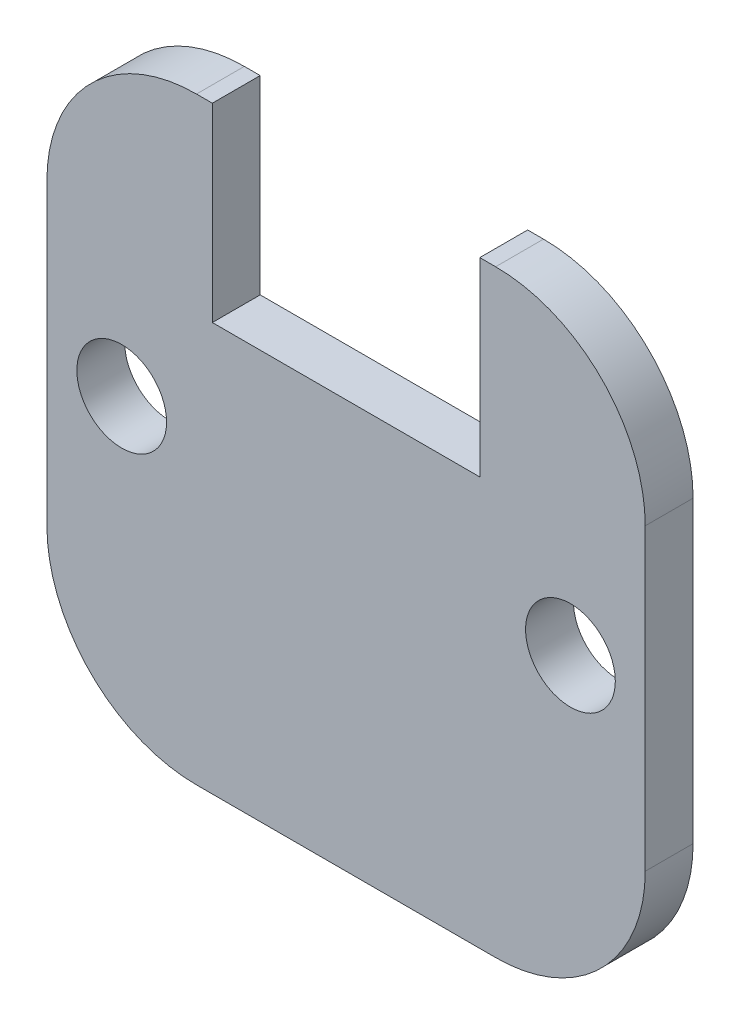
SolidWorks part; units mm, degrees
ref_plane "Front Plane" through (0, 0, 0) normal (0, 0, 1) x (1, 0, 0)
ref_plane "Top Plane" through (0, 0, 0) normal (0, 1, 0) x (1, 0, 0)
ref_plane "Right Plane" through (0, 0, 0) normal (1, 0, 0) x (0, 0, -1)
sketch "Sketch1" plane through (0, 0, 0) normal (0, 0, 1) x (1, 0, 0)
  line L0 (157.8919, 26.2701) -> (191.7747, 29.0915)
  line L1 (157.8919, 26.2701) -> (191.7747, 26.2701)
  line L2 (157.8919, 26.2701) -> (157.8919, 29.0915)
  line L3 (157.8919, 29.0915) -> (191.7747, 29.0915)
  line L4 (191.7747, 26.2701) -> (191.7747, 29.0915)
  line L5 (123.8919, 26.2701) -> (90.0092, 26.2701)
  line L6 (123.8919, 26.2701) -> (123.8919, 29.0915)
  line L7 (123.8919, 29.0915) -> (90.0092, 29.0915)
  line L8 (90.0092, 26.2701) -> (90.0092, 29.0915)
  line L9 (90.0092, 29.0915) -> (123.8919, 26.2701)
  line L10 (168.0919, 58.3601) -> (194.8735, 70.7292)
  line L11 (168.0919, 58.3601) -> (194.8735, 58.3601)
  line L12 (168.0919, 58.3601) -> (168.0919, 70.7292)
  line L13 (168.0919, 70.7292) -> (194.8735, 70.7292)
  line L14 (194.8735, 58.3601) -> (194.8735, 70.7292)
  line L15 (194.8735, 70.7292) -> (224.3587, 70.7292)
  line L16 (194.8735, 70.7292) -> (194.8735, 69.7923)
  line L17 (194.8735, 69.7923) -> (224.3587, 69.7923)
  line L18 (224.3587, 70.7292) -> (224.3587, 69.7923)
  line L19 (224.3587, 69.7923) -> (253.5106, 69.7923)
  line L20 (224.3587, 69.7923) -> (224.3587, 65.2742)
  line L21 (224.3587, 65.2742) -> (253.5106, 65.2742)
  line L22 (253.5106, 69.7923) -> (253.5106, 65.2742)
  line L23 (224.3587, 69.7923) -> (194.8735, 70.7292)
  line L24 (253.5106, 65.2742) -> (224.3587, 69.7923)
  line L25 (170.7502, 87.7401) -> (168.0919, 58.3601)
  line L26 (168.0919, 58.3601) -> (170.7502, 58.3601)
  line L27 (168.0919, 58.3601) -> (168.0919, 87.7401)
  line L28 (168.0919, 87.7401) -> (170.7502, 87.7401)
  line L29 (170.7502, 58.3601) -> (170.7502, 87.7401)
  line L30 (52.9966, 89.4705) -> (24.4119, 82.1791)
  line L31 (24.4119, 82.1791) -> (52.9966, 82.1791)
  line L32 (24.4119, 82.1791) -> (24.4119, 89.4705)
  line L33 (24.4119, 89.4705) -> (52.9966, 89.4705)
  line L34 (52.9966, 82.1791) -> (52.9966, 89.4705)
  line L35 (82.4966, 89.4705) -> (109.0019, 89.4705)
  line L36 (82.4966, 89.4705) -> (82.4966, 76.5201)
  line L37 (82.4966, 76.5201) -> (109.0019, 76.5201)
  line L38 (109.0019, 89.4705) -> (109.0019, 76.5201)
  line L39 (92.4554, 117.2387) -> (82.4966, 117.2387)
  line L40 (92.4554, 117.2387) -> (92.4554, 89.4705)
  line L41 (92.4554, 89.4705) -> (82.4966, 89.4705)
  line L42 (82.4966, 117.2387) -> (82.4966, 89.4705)
  line L43 (92.4554, 117.2387) -> (82.4966, 89.4705)
  line L44 (109.0019, 76.5201) -> (82.4966, 89.4705)
  circle A0 centre (123.8919, 26.2701) radius 14.25
  circle A1 centre (157.8919, 26.2701) radius 14.25
  circle A2 centre (90.0092, 29.0915) radius 14.25
  circle A3 centre (191.7747, 29.0915) radius 14.25
  circle A4 centre (82.4966, 89.4705) radius 11.25
  circle A5 centre (92.4554, 117.2387) radius 11.25
  circle A6 centre (52.9966, 89.4705) radius 11.25
  circle A7 centre (109.0019, 76.5201) radius 11.25
  circle A8 centre (24.4119, 82.1791) radius 11.25
  circle A9 centre (170.7502, 87.7401) radius 11.25
  circle A10 centre (168.0919, 58.3601) radius 11.25
  circle A11 centre (197.5318, 100.1092) radius 11.25
  circle A12 centre (194.8735, 70.7292) radius 11.25
  circle A13 centre (227.0169, 99.1723) radius 11.25
  circle A14 centre (224.3587, 69.7923) radius 11.25
  circle A15 centre (256.1689, 94.6541) radius 11.25
  circle A16 centre (253.5106, 65.2742) radius 11.25
  circle A17 centre (24.4119, 82.1791) radius 12
  circle A18 centre (52.9966, 89.4705) radius 12
  circle A19 centre (92.4554, 117.2387) radius 12
  circle A20 centre (82.4966, 89.4705) radius 12
  circle A21 centre (109.0019, 76.5201) radius 12
  circle A22 centre (168.0919, 58.3601) radius 12
  circle A23 centre (194.8735, 70.7292) radius 12
  circle A24 centre (224.3587, 69.7923) radius 12
  circle A25 centre (253.5106, 65.2742) radius 12
  circle A26 centre (256.1689, 94.6541) radius 12
  circle A27 centre (227.0169, 99.1723) radius 12
  circle A28 centre (197.5318, 100.1092) radius 12
  circle A29 centre (170.7502, 87.7401) radius 12
  circle A30 centre (191.7747, 29.0915) radius 15
  circle A31 centre (157.8919, 26.2701) radius 15
  circle A32 centre (123.8919, 26.2701) radius 15
  circle A33 centre (90.0092, 29.0915) radius 15
  circle A34 centre (173.429, 117.1182) radius 11.25
  circle A35 centre (173.429, 117.1182) radius 12
  dimension "D1" = 28.5
  dimension "D2" = 22.5
  dimension "D3" = 0.75
  dimension "D4" = 0.75
  dimension "D34" = 34
  dimension "D5" = 29.5
  dimension "D6" = 29.5
  dimension "D7" = 29.5
  dimension "D8" = 29.5
  dimension "D9" = 29.5
  dimension "D10" = 29.5
  dimension "D11" = 29.5
  dimension "D12" = 29.5
  dimension "D13" = 29.5
  dimension "D14" = 29.5
  dimension "D15" = 29.5
  dimension "D16" = 29.5
  dimension "D17" = 29.5
  dimension "D18" = 29.5
  dimension "D19" = 34
  dimension "D20" = 34
  dimension "D21" = 32.09
  dimension "D22" = 10.2
  dimension "D23" = 4.76
  dimension "D24" = 4.76
  dimension "D25" = 24.79
  dimension "D26" = 1.82
  dimension "D27" = 8.81
  dimension "D28" = 84.83
  dimension "D29" = 75.69
  dimension "D30" = 70.27
  dimension "D31" = 26.04
  dimension "D32" = 14.89
  dimension "D33" = 50.25
  dimension "D35" = 29.5
  dimension "D36" = 29.5
sketch "Sketch4" plane through (-30.2083, 20.075, 0) normal (0, 0, 1) x (0.9781, -0.2079, 0)
  line L0 (86.1706, 94.1917) -> (105.2206, 75.1417)
  line L1 (67.1206, 94.1917) -> (86.1706, 94.1917)
  line L2 (67.1206, 94.1917) -> (67.1206, 75.1417)
  line L3 (67.1206, 75.1417) -> (86.1706, 75.1417)
  line L4 (86.1706, 94.1917) -> (86.1706, 75.1417)
  line L5 (86.1706, 94.1917) -> (105.2206, 94.1917)
  line L6 (86.1706, 94.1917) -> (86.1706, 75.1417)
  line L7 (86.1706, 75.1417) -> (105.2206, 75.1417)
  line L8 (105.2206, 94.1917) -> (105.2206, 75.1417)
  line L9 (105.2206, 94.1917) -> (124.2706, 94.1917)
  line L10 (105.2206, 94.1917) -> (105.2206, 75.1417)
  line L11 (105.2206, 75.1417) -> (124.2706, 75.1417)
  line L12 (124.2706, 94.1917) -> (124.2706, 75.1417)
  line L13 (86.1706, 94.1917) -> (105.2206, 94.1917)
  line L14 (86.1706, 94.1917) -> (86.1706, 113.2417)
  line L15 (86.1706, 113.2417) -> (105.2206, 113.2417)
  line L16 (105.2206, 94.1917) -> (105.2206, 113.2417)
  line L17 (66.9585, 85.1784) -> (124.4326, 84.1551)
  point P14 (95.6956, 84.6667)
  point P15 (95.6956, 84.6667)
  dimension "D1" = 19.05
sketch "Sketch9" plane through (0, 0, 0) normal (0, 0, 1) x (1, 0, 0)
  line L1 (17.3619, 89.2291) -> (31.4619, 89.2291)
  line L2 (17.3619, 89.2291) -> (17.3619, 75.1291)
  line L3 (17.3619, 75.1291) -> (31.4619, 75.1291)
  line L4 (31.4619, 89.2291) -> (31.4619, 75.1291)
  line L5 (45.9466, 96.5205) -> (60.0466, 96.5205)
  line L6 (45.9466, 96.5205) -> (45.9466, 82.4205)
  line L7 (45.9466, 82.4205) -> (60.0466, 82.4205)
  line L8 (60.0466, 96.5205) -> (60.0466, 82.4205)
  line L9 (75.4466, 96.5205) -> (89.5466, 96.5205)
  line L10 (75.4466, 96.5205) -> (75.4466, 82.4205)
  line L11 (75.4466, 82.4205) -> (89.5466, 82.4205)
  line L12 (89.5466, 96.5205) -> (89.5466, 82.4205)
  line L13 (101.9519, 83.5701) -> (116.0519, 83.5701)
  line L14 (101.9519, 83.5701) -> (101.9519, 69.4701)
  line L15 (101.9519, 69.4701) -> (116.0519, 69.4701)
  line L16 (116.0519, 83.5701) -> (116.0519, 69.4701)
  line L17 (85.4054, 124.2887) -> (99.5054, 124.2887)
  line L18 (85.4054, 124.2887) -> (85.4054, 110.1887)
  line L19 (85.4054, 110.1887) -> (99.5054, 110.1887)
  line L20 (99.5054, 124.2887) -> (99.5054, 110.1887)
  line L21 (82.9592, 36.1415) -> (97.0592, 36.1415)
  line L22 (82.9592, 36.1415) -> (82.9592, 22.0415)
  line L23 (82.9592, 22.0415) -> (97.0592, 22.0415)
  line L24 (97.0592, 36.1415) -> (97.0592, 22.0415)
  line L25 (116.8419, 33.3201) -> (130.9419, 33.3201)
  line L26 (116.8419, 33.3201) -> (116.8419, 19.2201)
  line L27 (116.8419, 19.2201) -> (130.9419, 19.2201)
  line L28 (130.9419, 33.3201) -> (130.9419, 19.2201)
  line L29 (150.8419, 33.3201) -> (164.9419, 33.3201)
  line L30 (150.8419, 33.3201) -> (150.8419, 19.2201)
  line L31 (150.8419, 19.2201) -> (164.9419, 19.2201)
  line L32 (164.9419, 33.3201) -> (164.9419, 19.2201)
  line L33 (184.7247, 36.1415) -> (198.8247, 36.1415)
  line L34 (184.7247, 36.1415) -> (184.7247, 22.0415)
  line L35 (184.7247, 22.0415) -> (198.8247, 22.0415)
  line L36 (198.8247, 36.1415) -> (198.8247, 22.0415)
  line L37 (260.5606, 58.2242) -> (246.4606, 58.2242)
  line L38 (260.5606, 58.2242) -> (260.5606, 72.3242)
  line L39 (260.5606, 72.3242) -> (246.4606, 72.3242)
  line L40 (246.4606, 58.2242) -> (246.4606, 72.3242)
  line L41 (217.3087, 76.8423) -> (231.4087, 76.8423)
  line L42 (217.3087, 76.8423) -> (217.3087, 62.7423)
  line L43 (217.3087, 62.7423) -> (231.4087, 62.7423)
  line L44 (231.4087, 76.8423) -> (231.4087, 62.7423)
  line L45 (187.8235, 77.7792) -> (201.9235, 77.7792)
  line L46 (187.8235, 77.7792) -> (187.8235, 63.6792)
  line L47 (187.8235, 63.6792) -> (201.9235, 63.6792)
  line L48 (201.9235, 77.7792) -> (201.9235, 63.6792)
  line L49 (161.0419, 65.4101) -> (175.1419, 65.4101)
  line L50 (161.0419, 65.4101) -> (161.0419, 51.3101)
  line L51 (161.0419, 51.3101) -> (175.1419, 51.3101)
  line L52 (175.1419, 65.4101) -> (175.1419, 51.3101)
  line L53 (163.7002, 94.7901) -> (177.8002, 94.7901)
  line L54 (163.7002, 94.7901) -> (163.7002, 80.6901)
  line L55 (163.7002, 80.6901) -> (177.8002, 80.6901)
  line L56 (177.8002, 94.7901) -> (177.8002, 80.6901)
  line L57 (190.4818, 107.1592) -> (204.5818, 107.1592)
  line L58 (190.4818, 107.1592) -> (190.4818, 93.0592)
  line L59 (190.4818, 93.0592) -> (204.5818, 93.0592)
  line L60 (204.5818, 107.1592) -> (204.5818, 93.0592)
  line L61 (219.9669, 106.2223) -> (234.0669, 106.2223)
  line L62 (219.9669, 106.2223) -> (219.9669, 92.1223)
  line L63 (219.9669, 92.1223) -> (234.0669, 92.1223)
  line L64 (234.0669, 106.2223) -> (234.0669, 92.1223)
  line L65 (249.1189, 101.7041) -> (263.2189, 101.7041)
  line L66 (249.1189, 101.7041) -> (249.1189, 87.6041)
  line L67 (249.1189, 87.6041) -> (263.2189, 87.6041)
  line L68 (263.2189, 101.7041) -> (263.2189, 87.6041)
  line L69 (166.379, 124.1682) -> (180.479, 124.1682)
  line L70 (166.379, 124.1682) -> (166.379, 110.0682)
  line L71 (166.379, 110.0682) -> (180.479, 110.0682)
  line L72 (180.479, 124.1682) -> (180.479, 110.0682)
  point P72 (24.4119, 89.2291)
  point P74 (52.9966, 96.5205)
  point P76 (82.4966, 96.5205)
  point P78 (92.4554, 124.2887)
  point P80 (109.0019, 83.5701)
  point P82 (90.0092, 36.1415)
  point P84 (123.8919, 33.3201)
  point P86 (157.8919, 33.3201)
  point P88 (191.7747, 36.1415)
  point P90 (168.0919, 65.4101)
  point P92 (170.7502, 94.7901)
  point P94 (173.429, 124.1682)
  point P96 (197.5318, 107.1592)
  point P98 (227.0169, 106.2223)
  point P100 (256.1689, 101.7041)
  point P102 (194.8735, 77.7792)
  point P104 (224.3587, 76.8423)
  point P106 (253.5106, 72.3242)
  point P108 (17.3619, 82.1791)
  point P109 (45.9466, 89.4705)
  point P110 (75.4466, 89.4705)
  point P111 (101.9519, 76.5201)
  point P112 (85.4054, 117.2387)
  point P113 (82.9592, 29.0915)
  point P114 (116.8419, 26.2701)
  point P115 (150.8419, 26.2701)
  point P116 (184.7247, 29.0915)
  point P118 (161.0419, 58.3601)
  point P119 (187.8235, 70.7292)
  point P120 (217.3087, 69.7923)
  point P121 (246.4606, 65.2742)
  point P122 (163.7002, 87.7401)
  point P123 (190.4818, 100.1092)
  point P124 (219.9669, 99.1723)
  point P125 (249.1189, 94.6541)
  point P126 (166.379, 117.1182)
  dimension "D1" = 14.1
sketch "Sketch10" plane through (-22.0981, 19.3454, 0) normal (0, 0, 1) x (0.9781, -0.2079, 0)
  line L1 (61.5108, 90.7441) -> (75.6108, 90.7441)
  line L2 (61.5108, 90.7441) -> (61.5108, 76.6441)
  line L3 (61.5108, 76.6441) -> (75.6108, 76.6441)
  line L4 (75.6108, 90.7441) -> (75.6108, 76.6441)
  line L5 (80.5608, 90.7441) -> (94.6608, 90.7441)
  line L6 (80.5608, 90.7441) -> (80.5608, 76.6441)
  line L7 (80.5608, 76.6441) -> (94.6608, 76.6441)
  line L8 (94.6608, 90.7441) -> (94.6608, 76.6441)
  line L9 (99.6108, 90.7441) -> (113.7108, 90.7441)
  line L10 (99.6108, 90.7441) -> (99.6108, 76.6441)
  line L11 (99.6108, 76.6441) -> (113.7108, 76.6441)
  line L12 (113.7108, 90.7441) -> (113.7108, 76.6441)
  line L13 (80.5608, 109.7941) -> (94.6608, 109.7941)
  line L14 (80.5608, 109.7941) -> (80.5608, 95.6941)
  line L15 (80.5608, 95.6941) -> (94.6608, 95.6941)
  line L16 (94.6608, 109.7941) -> (94.6608, 95.6941)
  line L17 (50.5121, 89.6359) -> (53.4436, 75.8441) construction
  line L18 (59.0358, 93.2191) -> (78.0858, 93.2191) construction
  line L19 (78.0858, 112.2691) -> (97.1358, 112.2691) construction
  line L20 (97.1358, 93.2191) -> (116.1858, 93.2191) construction
  line L21 (78.0858, 93.2191) -> (78.0858, 112.2691) construction
  line L23 (59.0358, 93.2191) -> (59.0358, 74.1691) construction
  point P16 (75.6108, 83.6941)
  point P17 (94.6608, 83.6941)
  point P18 (113.7108, 83.6941)
  point P19 (87.6108, 90.7441)
  point P20 (87.6108, 109.7941)
  point P23 (68.5608, 90.7441)
  point P26 (68.5608, 93.2191)
  point P29 (87.6108, 112.2691)
  point P30 (106.6608, 90.7441)
  point P33 (106.6608, 93.2191)
  point P34 (80.5608, 102.7441)
  point P37 (78.0858, 102.7441)
  point P42 (59.0358, 83.6941)
  point P43 (61.5108, 83.6941)
sketch "Sketch14" plane through (0, 0, 0) normal (0, 0, 1) x (1, 0, 0)
  line L0 (165.1144, 80.6901) -> (163.7002, 82.1043)
  line L1 (163.7002, 93.3758) -> (165.1144, 94.7901)
  line L2 (177.8002, 93.3758) -> (176.386, 94.7901)
  line L3 (179.0648, 110.0682) -> (180.479, 111.4824)
  line L4 (166.379, 111.4824) -> (167.7932, 110.0682)
  line L5 (166.379, 122.754) -> (167.7932, 124.1682)
  line L6 (179.0648, 124.1682) -> (180.479, 122.754)
  line L7 (203.1676, 93.0592) -> (204.5818, 94.4734)
  line L8 (17.3619, 89.2291) -> (17.3619, 75.1291) construction
  line L9 (17.3619, 89.2291) -> (31.4619, 89.2291) construction
  line L10 (17.3619, 87.8149) -> (18.7761, 89.2291)
  line L11 (17.3619, 75.1291) -> (31.4619, 75.1291) construction
  line L12 (31.4619, 89.2291) -> (31.4619, 75.1291) construction
  line L13 (45.9466, 96.5205) -> (60.0466, 96.5205) construction
  line L14 (60.0466, 96.5205) -> (60.0466, 82.4205) construction
  line L15 (45.9466, 96.5205) -> (45.9466, 82.4205) construction
  line L16 (45.9466, 82.4205) -> (60.0466, 82.4205) construction
  line L17 (85.4054, 124.2887) -> (85.4054, 110.1887) construction
  line L18 (85.4054, 124.2887) -> (99.5054, 124.2887) construction
  line L19 (99.5054, 124.2887) -> (99.5054, 110.1887) construction
  line L20 (85.4054, 110.1887) -> (99.5054, 110.1887) construction
  line L21 (101.9519, 83.5701) -> (101.9519, 69.4701) construction
  line L22 (101.9519, 83.5701) -> (116.0519, 83.5701) construction
  line L23 (116.0519, 83.5701) -> (116.0519, 69.4701) construction
  line L24 (101.9519, 69.4701) -> (116.0519, 69.4701) construction
  line L25 (91.2712, 73.6044) -> (105.0631, 70.6729) construction
  line L26 (107.9947, 84.4647) -> (105.0631, 70.6729) construction
  line L27 (94.2028, 87.3963) -> (107.9947, 84.4647) construction
  line L28 (94.2028, 87.3963) -> (91.2712, 73.6044) construction
  line L29 (72.6375, 77.5651) -> (86.4294, 74.6336) construction
  line L30 (89.361, 88.4255) -> (86.4294, 74.6336) construction
  line L31 (75.5691, 91.357) -> (89.361, 88.4255) construction
  line L32 (75.5691, 91.357) -> (72.6375, 77.5651) construction
  line L33 (56.9354, 95.3177) -> (54.0038, 81.5259) construction
  line L34 (56.9354, 95.3177) -> (70.7273, 92.3862) construction
  line L35 (70.7273, 92.3862) -> (67.7957, 78.5943) construction
  line L36 (54.0038, 81.5259) -> (67.7957, 78.5943) construction
  line L37 (76.5983, 96.1988) -> (90.3901, 93.2673) construction
  line L38 (93.3217, 107.0592) -> (90.3901, 93.2673) construction
  line L39 (79.5298, 109.9907) -> (76.5983, 96.1988) construction
  line L40 (79.5298, 109.9907) -> (93.3217, 107.0592) construction
  line L41 (82.9592, 36.1415) -> (82.9592, 22.0415) construction
  line L42 (82.9592, 36.1415) -> (97.0592, 36.1415) construction
  line L43 (82.9592, 22.0415) -> (97.0592, 22.0415) construction
  line L44 (97.0592, 36.1415) -> (97.0592, 22.0415) construction
  line L45 (116.8419, 33.3201) -> (116.8419, 19.2201) construction
  line L46 (116.8419, 33.3201) -> (130.9419, 33.3201) construction
  line L47 (116.8419, 19.2201) -> (130.9419, 19.2201) construction
  line L48 (130.9419, 33.3201) -> (130.9419, 19.2201) construction
  line L49 (150.8419, 33.3201) -> (150.8419, 19.2201) construction
  line L50 (150.8419, 33.3201) -> (164.9419, 33.3201) construction
  line L51 (164.9419, 33.3201) -> (164.9419, 19.2201) construction
  line L52 (150.8419, 19.2201) -> (164.9419, 19.2201) construction
  line L53 (184.7247, 36.1415) -> (184.7247, 22.0415) construction
  line L54 (184.7247, 22.0415) -> (198.8247, 22.0415) construction
  line L55 (198.8247, 36.1415) -> (198.8247, 22.0415) construction
  line L56 (184.7247, 36.1415) -> (198.8247, 36.1415) construction
  line L57 (161.0419, 65.4101) -> (175.1419, 65.4101) construction
  line L58 (175.1419, 65.4101) -> (175.1419, 51.3101) construction
  line L59 (161.0419, 51.3101) -> (175.1419, 51.3101) construction
  line L60 (161.0419, 65.4101) -> (161.0419, 51.3101) construction
  line L61 (187.8235, 77.7792) -> (187.8235, 63.6792) construction
  line L62 (187.8235, 77.7792) -> (201.9235, 77.7792) construction
  line L63 (187.8235, 63.6792) -> (201.9235, 63.6792) construction
  line L64 (201.9235, 77.7792) -> (201.9235, 63.6792) construction
  line L65 (217.3087, 76.8423) -> (217.3087, 62.7423) construction
  line L66 (217.3087, 76.8423) -> (231.4087, 76.8423) construction
  line L67 (231.4087, 76.8423) -> (231.4087, 62.7423) construction
  line L68 (217.3087, 62.7423) -> (231.4087, 62.7423) construction
  line L69 (260.5606, 58.2242) -> (246.4606, 58.2242) construction
  line L70 (260.5606, 58.2242) -> (260.5606, 72.3242) construction
  line L71 (246.4606, 58.2242) -> (246.4606, 72.3242) construction
  line L72 (260.5606, 72.3242) -> (246.4606, 72.3242) construction
  line L73 (249.1189, 101.7041) -> (263.2189, 101.7041) construction
  line L74 (263.2189, 101.7041) -> (263.2189, 87.6041) construction
  line L75 (249.1189, 87.6041) -> (263.2189, 87.6041) construction
  line L76 (249.1189, 101.7041) -> (249.1189, 87.6041) construction
  line L77 (219.9669, 106.2223) -> (219.9669, 92.1223) construction
  line L78 (219.9669, 106.2223) -> (234.0669, 106.2223) construction
  line L79 (234.0669, 106.2223) -> (234.0669, 92.1223) construction
  line L80 (219.9669, 92.1223) -> (234.0669, 92.1223) construction
  line L81 (190.4818, 107.1592) -> (204.5818, 107.1592) construction
  line L82 (204.5818, 107.1592) -> (204.5818, 93.0592) construction
  line L83 (190.4818, 93.0592) -> (204.5818, 93.0592) construction
  line L84 (190.4818, 107.1592) -> (190.4818, 93.0592) construction
  line L85 (163.7002, 94.7901) -> (177.8002, 94.7901) construction
  line L86 (177.8002, 94.7901) -> (177.8002, 80.6901) construction
  line L87 (163.7002, 80.6901) -> (177.8002, 80.6901) construction
  line L88 (163.7002, 94.7901) -> (163.7002, 80.6901) construction
  line L89 (180.479, 124.1682) -> (180.479, 110.0682) construction
  line L90 (166.379, 110.0682) -> (180.479, 110.0682) construction
  line L91 (166.379, 124.1682) -> (166.379, 110.0682) construction
  line L92 (166.379, 124.1682) -> (180.479, 124.1682) construction
  line L93 (17.3619, 76.5433) -> (18.7761, 75.1291)
  line L94 (30.0477, 75.1291) -> (31.4619, 76.5433)
  line L95 (31.4619, 87.8149) -> (30.0477, 89.2291)
  line L96 (45.9466, 95.1063) -> (47.3608, 96.5205)
  line L97 (45.9466, 83.8347) -> (47.3608, 82.4205)
  line L98 (54.2979, 82.9092) -> (55.3871, 81.2318)
  line L99 (58.6323, 82.4205) -> (60.0466, 83.8347)
  line L100 (56.6413, 93.9344) -> (58.3187, 95.0237)
  line L101 (58.6323, 96.5205) -> (60.0466, 95.1063)
  line L102 (69.3439, 92.6802) -> (70.4332, 91.0029)
  line L103 (68.0897, 79.9776) -> (66.4124, 78.8883)
  line L104 (75.2751, 89.9737) -> (76.9524, 91.063)
  line L105 (72.9316, 78.9484) -> (74.0208, 77.2711)
  line L106 (85.0461, 74.9276) -> (86.7234, 76.0169)
  line L107 (89.0669, 87.0421) -> (87.9777, 88.7195)
  line L108 (89.0068, 93.5613) -> (90.6842, 94.6506)
  line L109 (76.8923, 97.5822) -> (77.9816, 95.9048)
  line L110 (91.9384, 107.3532) -> (93.0277, 105.6759)
  line L111 (79.2358, 108.6074) -> (80.9131, 109.6967)
  line L112 (85.4054, 111.6029) -> (86.8196, 110.1887)
  line L113 (98.0912, 110.1887) -> (99.5054, 111.6029)
  line L114 (98.0912, 124.2887) -> (99.5054, 122.8745)
  line L115 (85.4054, 122.8745) -> (86.8196, 124.2887)
  line L116 (93.9088, 86.013) -> (95.5861, 87.1023)
  line L117 (91.5653, 74.9877) -> (92.6546, 73.3104)
  line L118 (103.6798, 70.9669) -> (105.3572, 72.0562)
  line L119 (106.6114, 84.7588) -> (107.7006, 83.0814)
  line L120 (101.9519, 82.1559) -> (103.3662, 83.5701)
  line L121 (101.9519, 70.8843) -> (103.3662, 69.4701)
  line L122 (114.6377, 69.4701) -> (116.0519, 70.8843)
  line L123 (116.0519, 82.1559) -> (114.6377, 83.5701)
  line L124 (82.9592, 34.7272) -> (84.3734, 36.1415)
  line L125 (82.9592, 23.4557) -> (84.3734, 22.0415)
  line L126 (95.645, 22.0415) -> (97.0592, 23.4557)
  line L127 (97.0592, 34.7272) -> (95.645, 36.1415)
  line L128 (116.8419, 31.9059) -> (118.2562, 33.3201)
  line L129 (116.8419, 20.6343) -> (118.2562, 19.2201)
  line L130 (129.5277, 19.2201) -> (130.9419, 20.6343)
  line L131 (130.9419, 31.9059) -> (129.5277, 33.3201)
  line L132 (150.8419, 31.9059) -> (152.2562, 33.3201)
  line L133 (150.8419, 20.6343) -> (152.2562, 19.2201)
  line L134 (163.5277, 19.2201) -> (164.9419, 20.6343)
  line L135 (164.9419, 31.9059) -> (163.5277, 33.3201)
  line L136 (184.7247, 34.7272) -> (186.1389, 36.1415)
  line L137 (184.7247, 23.4557) -> (186.1389, 22.0415)
  line L138 (197.4105, 22.0415) -> (198.8247, 23.4557)
  line L139 (198.8247, 34.7272) -> (197.4105, 36.1415)
  line L140 (173.7277, 51.3101) -> (175.1419, 52.7243)
  line L141 (161.0419, 52.7243) -> (162.4562, 51.3101)
  line L142 (161.0419, 63.9959) -> (162.4562, 65.4101)
  line L143 (173.7277, 65.4101) -> (175.1419, 63.9959)
  line L144 (187.8235, 65.0934) -> (189.2378, 63.6792)
  line L145 (200.5093, 63.6792) -> (201.9235, 65.0934)
  line L146 (200.5093, 77.7792) -> (201.9235, 76.365)
  line L147 (187.8235, 76.365) -> (189.2378, 77.7792)
  line L148 (176.386, 80.6901) -> (177.8002, 82.1043)
  line L149 (204.5818, 105.745) -> (203.1676, 107.1592)
  line L150 (191.896, 107.1592) -> (190.4818, 105.745)
  line L151 (190.4818, 94.4734) -> (191.896, 93.0592)
  line L152 (219.9669, 104.8081) -> (221.3812, 106.2223)
  line L153 (232.6527, 106.2223) -> (234.0669, 104.8081)
  line L154 (234.0669, 93.5365) -> (232.6527, 92.1223)
  line L155 (219.9669, 93.5365) -> (221.3812, 92.1223)
  line L156 (229.9944, 76.8423) -> (231.4087, 75.4281)
  line L157 (217.3087, 75.4281) -> (218.7229, 76.8423)
  line L158 (217.3087, 64.1565) -> (218.7229, 62.7423)
  line L159 (229.9944, 62.7423) -> (231.4087, 64.1565)
  line L160 (259.1464, 72.3242) -> (260.5606, 70.9099)
  line L161 (246.4606, 70.9099) -> (247.8748, 72.3242)
  line L162 (259.1464, 58.2242) -> (260.5606, 59.6384)
  line L163 (247.8748, 58.2242) -> (246.4606, 59.6384)
  line L164 (261.8047, 87.6041) -> (263.2189, 89.0183)
  line L165 (249.1189, 89.0183) -> (250.5331, 87.6041)
  line L166 (249.1189, 100.2899) -> (250.5331, 101.7041)
  line L167 (261.8047, 101.7041) -> (263.2189, 100.2899)
  line L168 (75.4466, 96.5205) -> (75.4466, 82.4205) construction
  line L169 (75.4466, 96.5205) -> (89.5466, 96.5205) construction
  line L170 (89.5466, 96.5205) -> (89.5466, 82.4205) construction
  line L171 (75.4466, 82.4205) -> (89.5466, 82.4205) construction
  line L172 (76.8608, 96.5205) -> (75.4466, 95.1063)
  line L173 (88.1323, 96.5205) -> (89.5466, 95.1063)
  line L174 (89.5466, 83.8347) -> (88.1323, 82.4205)
  line L175 (75.4466, 83.8347) -> (76.8608, 82.4205)
  arc A0 (17.3619, 87.8149) -> (18.7761, 89.2291) centre (18.069, 88.522) cw
  arc A1 (18.7761, 75.1291) -> (17.3619, 76.5433) centre (18.069, 75.8362) cw
  arc A2 (31.4619, 76.5433) -> (30.0477, 75.1291) centre (30.7548, 75.8362) cw
  arc A3 (30.0477, 89.2291) -> (31.4619, 87.8149) centre (30.7548, 88.522) cw
  arc A4 (58.6323, 96.5205) -> (60.0466, 95.1063) centre (59.3394, 95.8134) cw
  arc A5 (45.9466, 95.1063) -> (47.3608, 96.5205) centre (46.6537, 95.8134) cw
  arc A6 (47.3608, 82.4205) -> (45.9466, 83.8347) centre (46.6537, 83.1276) cw
  arc A7 (60.0466, 83.8347) -> (58.6323, 82.4205) centre (59.3394, 83.1276) cw
  arc A8 (85.4054, 122.8745) -> (86.8196, 124.2887) centre (86.1125, 123.5816) cw
  arc A9 (98.0912, 124.2887) -> (99.5054, 122.8745) centre (98.7983, 123.5816) cw
  arc A10 (99.5054, 111.6029) -> (98.0912, 110.1887) centre (98.7983, 110.8958) cw
  arc A11 (85.4054, 111.6029) -> (86.8196, 110.1887) centre (86.1125, 110.8958) ccw
  arc A12 (101.9519, 82.1559) -> (103.3662, 83.5701) centre (102.6591, 82.863) cw
  arc A13 (114.6377, 83.5701) -> (116.0519, 82.1559) centre (115.3448, 82.863) cw
  arc A14 (116.0519, 70.8843) -> (114.6377, 69.4701) centre (115.3448, 70.1772) cw
  arc A15 (101.9519, 70.8843) -> (103.3662, 69.4701) centre (102.6591, 70.1772) ccw
  arc A16 (103.6798, 70.9669) -> (105.3572, 72.0562) centre (104.5185, 71.5115) ccw
  arc A17 (106.6114, 84.7588) -> (107.7006, 83.0814) centre (107.156, 83.9201) cw
  arc A18 (93.9088, 86.013) -> (95.5861, 87.1023) centre (94.7474, 86.5576) cw
  arc A19 (91.5653, 74.9877) -> (92.6546, 73.3104) centre (92.1099, 74.1491) ccw
  arc A20 (85.0461, 74.9276) -> (86.7234, 76.0169) centre (85.8848, 75.4722) ccw
  arc A21 (87.9777, 88.7195) -> (89.0669, 87.0421) centre (88.5223, 87.8808) cw
  arc A22 (75.2751, 89.9737) -> (76.9524, 91.063) centre (76.1137, 90.5183) cw
  arc A23 (72.9316, 78.9484) -> (74.0208, 77.2711) centre (73.4762, 78.1098) ccw
  arc A24 (56.6413, 93.9344) -> (58.3187, 95.0237) centre (57.48, 94.4791) cw
  arc A25 (69.3439, 92.6802) -> (70.4332, 91.0029) centre (69.8886, 91.8415) cw
  arc A26 (68.0897, 79.9776) -> (66.4124, 78.8883) centre (67.2511, 79.433) cw
  arc A27 (54.2979, 82.9092) -> (55.3871, 81.2318) centre (54.8425, 82.0705) ccw
  arc A28 (89.0068, 93.5613) -> (90.6842, 94.6506) centre (89.8455, 94.106) ccw
  arc A29 (76.8923, 97.5822) -> (77.9816, 95.9048) centre (77.4369, 96.7435) ccw
  arc A30 (79.2358, 108.6074) -> (80.9131, 109.6967) centre (80.0744, 109.1521) cw
  arc A31 (91.9384, 107.3532) -> (93.0277, 105.6759) centre (92.483, 106.5145) cw
  arc A32 (82.9592, 34.7272) -> (84.3734, 36.1415) centre (83.6663, 35.4344) cw
  arc A33 (82.9592, 23.4557) -> (84.3734, 22.0415) centre (83.6663, 22.7486) ccw
  arc A34 (95.645, 22.0415) -> (97.0592, 23.4557) centre (96.3521, 22.7486) ccw
  arc A35 (95.645, 36.1415) -> (97.0592, 34.7272) centre (96.3521, 35.4344) cw
  arc A36 (116.8419, 31.9059) -> (118.2562, 33.3201) centre (117.5491, 32.613) cw
  arc A37 (116.8419, 20.6343) -> (118.2562, 19.2201) centre (117.5491, 19.9272) ccw
  arc A38 (129.5277, 19.2201) -> (130.9419, 20.6343) centre (130.2348, 19.9272) ccw
  arc A39 (129.5277, 33.3201) -> (130.9419, 31.9059) centre (130.2348, 32.613) cw
  arc A40 (150.8419, 31.9059) -> (152.2562, 33.3201) centre (151.5491, 32.613) cw
  arc A41 (163.5277, 33.3201) -> (164.9419, 31.9059) centre (164.2348, 32.613) cw
  arc A42 (164.9419, 20.6343) -> (163.5277, 19.2201) centre (164.2348, 19.9272) cw
  arc A43 (150.8419, 20.6343) -> (152.2562, 19.2201) centre (151.5491, 19.9272) ccw
  arc A44 (184.7247, 23.4557) -> (186.1389, 22.0415) centre (185.4318, 22.7486) ccw
  arc A45 (197.4105, 22.0415) -> (198.8247, 23.4557) centre (198.1176, 22.7486) ccw
  arc A46 (197.4105, 36.1415) -> (198.8247, 34.7272) centre (198.1176, 35.4344) cw
  arc A47 (184.7247, 34.7272) -> (186.1389, 36.1415) centre (185.4318, 35.4344) cw
  arc A48 (173.7277, 65.4101) -> (175.1419, 63.9959) centre (174.4348, 64.703) cw
  arc A49 (175.1419, 52.7243) -> (173.7277, 51.3101) centre (174.4348, 52.0172) cw
  arc A50 (161.0419, 52.7243) -> (162.4562, 51.3101) centre (161.7491, 52.0172) ccw
  arc A51 (161.0419, 63.9959) -> (162.4562, 65.4101) centre (161.7491, 64.703) cw
  arc A52 (187.8235, 76.365) -> (189.2378, 77.7792) centre (188.5306, 77.0721) cw
  arc A53 (187.8235, 65.0934) -> (189.2378, 63.6792) centre (188.5306, 64.3863) ccw
  arc A54 (200.5093, 63.6792) -> (201.9235, 65.0934) centre (201.2164, 64.3863) ccw
  arc A55 (200.5093, 77.7792) -> (201.9235, 76.365) centre (201.2164, 77.0721) cw
  arc A56 (217.3087, 75.4281) -> (218.7229, 76.8423) centre (218.0158, 76.1352) cw
  arc A57 (229.9944, 76.8423) -> (231.4087, 75.4281) centre (230.7016, 76.1352) cw
  arc A58 (231.4087, 64.1565) -> (229.9944, 62.7423) centre (230.7016, 63.4494) cw
  arc A59 (217.3087, 64.1565) -> (218.7229, 62.7423) centre (218.0158, 63.4494) ccw
  arc A60 (259.1464, 58.2242) -> (260.5606, 59.6384) centre (259.8535, 58.9313) ccw
  arc A61 (246.4606, 59.6384) -> (247.8748, 58.2242) centre (247.1677, 58.9313) ccw
  arc A62 (246.4606, 70.9099) -> (247.8748, 72.3242) centre (247.1677, 71.617) cw
  arc A63 (259.1464, 72.3242) -> (260.5606, 70.9099) centre (259.8535, 71.617) cw
  arc A64 (261.8047, 101.7041) -> (263.2189, 100.2899) centre (262.5118, 100.997) cw
  arc A65 (263.2189, 89.0183) -> (261.8047, 87.6041) centre (262.5118, 88.3112) cw
  arc A66 (250.5331, 87.6041) -> (249.1189, 89.0183) centre (249.826, 88.3112) cw
  arc A67 (249.1189, 100.2899) -> (250.5331, 101.7041) centre (249.826, 100.997) cw
  arc A68 (219.9669, 104.8081) -> (221.3812, 106.2223) centre (220.674, 105.5152) cw
  arc A69 (232.6527, 106.2223) -> (234.0669, 104.8081) centre (233.3598, 105.5152) cw
  arc A70 (234.0669, 93.5365) -> (232.6527, 92.1223) centre (233.3598, 92.8294) cw
  arc A71 (221.3812, 92.1223) -> (219.9669, 93.5365) centre (220.674, 92.8294) cw
  arc A72 (203.1676, 107.1592) -> (204.5818, 105.745) centre (203.8747, 106.4521) cw
  arc A73 (204.5818, 94.4734) -> (203.1676, 93.0592) centre (203.8747, 93.7663) cw
  arc A74 (191.896, 93.0592) -> (190.4818, 94.4734) centre (191.1889, 93.7663) cw
  arc A75 (190.4818, 105.745) -> (191.896, 107.1592) centre (191.1889, 106.4521) cw
  arc A76 (176.386, 94.7901) -> (177.8002, 93.3758) centre (177.0931, 94.0829) cw
  arc A77 (177.8002, 82.1043) -> (176.386, 80.6901) centre (177.0931, 81.3972) cw
  arc A78 (165.1144, 80.6901) -> (163.7002, 82.1043) centre (164.4073, 81.3972) cw
  arc A79 (163.7002, 93.3758) -> (165.1144, 94.7901) centre (164.4073, 94.0829) cw
  arc A80 (180.479, 111.4824) -> (179.0648, 110.0682) centre (179.7719, 110.7753) cw
  arc A81 (167.7932, 110.0682) -> (166.379, 111.4824) centre (167.0861, 110.7753) cw
  arc A82 (179.0648, 124.1682) -> (180.479, 122.754) centre (179.7719, 123.4611) cw
  arc A83 (166.379, 122.754) -> (167.7932, 124.1682) centre (167.0861, 123.4611) cw
  arc A84 (75.4466, 95.1063) -> (76.8608, 96.5205) centre (76.1537, 95.8134) cw
  arc A85 (88.1323, 96.5205) -> (89.5466, 95.1063) centre (88.8394, 95.8134) cw
  arc A86 (89.5466, 83.8347) -> (88.1323, 82.4205) centre (88.8394, 83.1276) cw
  arc A87 (76.8608, 82.4205) -> (75.4466, 83.8347) centre (76.1537, 83.1276) cw
  dimension "D1" = 45
  dimension "D2" = 1
  dimension "D71" = 45
  dimension "D3" = 45
  dimension "D4" = 45
  dimension "D5" = 45
  dimension "D6" = 45
  dimension "D7" = 45
  dimension "D8" = 45
  dimension "D9" = 45
  dimension "D10" = 45
  dimension "D11" = 45
  dimension "D12" = 45
  dimension "D13" = 45
  dimension "D14" = 45
  dimension "D15" = 45
  dimension "D16" = 45
  dimension "D17" = 45
  dimension "D18" = 45
  dimension "D19" = 45
  dimension "D20" = 45
  dimension "D21" = 45
  dimension "D22" = 45
  dimension "D23" = 45
  dimension "D24" = 45
  dimension "D25" = 45
  dimension "D26" = 45
  dimension "D27" = 45
  dimension "D28" = 45
  dimension "D29" = 45
  dimension "D30" = 45
  dimension "D31" = 45
  dimension "D32" = 45
  dimension "D33" = 45
  dimension "D34" = 45
  dimension "D35" = 45
  dimension "D36" = 45
  dimension "D37" = 45
  dimension "D38" = 45
  dimension "D39" = 45
  dimension "D40" = 45
  dimension "D41" = 45
  dimension "D42" = 45
  dimension "D43" = 45
  dimension "D44" = 45
  dimension "D45" = 45
  dimension "D46" = 45
  dimension "D47" = 45
  dimension "D48" = 45
  dimension "D49" = 45
  dimension "D50" = 45
  dimension "D51" = 45
  dimension "D52" = 45
  dimension "D53" = 45
  dimension "D54" = 45
  dimension "D55" = 45
  dimension "D56" = 45
  dimension "D57" = 45
  dimension "D58" = 45
  dimension "D59" = 45
  dimension "D60" = 45
  dimension "D61" = 45
  dimension "D62" = 45
  dimension "D63" = 45
  dimension "D64" = 45
  dimension "D65" = 45
  dimension "D66" = 45
  dimension "D67" = 45
  dimension "D68" = 45
  dimension "D69" = 45
  dimension "D70" = 45
  dimension "D72" = 45
  dimension "D73" = 45
  dimension "D74" = 45
  dimension "D75" = 45
  dimension "D76" = 45
  dimension "D77" = 45
  dimension "D78" = 45
  dimension "D79" = 45
  dimension "D80" = 45
  dimension "D81" = 45
  dimension "D82" = 45
  dimension "D83" = 45
  dimension "D84" = 45
  dimension "D85" = 45
  dimension "D86" = 45
  dimension "D87" = 45
  dimension "D88" = 45
  dimension "D89" = 45
sketch "Sketch16" plane through (0, 0, 0) normal (0, 0, 1) x (1, 0, 0)
  line L0 (81.0092, 30.6915) -> (99.0092, 30.6915)
  line L5 (17.3619, 89.2291) -> (17.3619, 75.1291) construction
  line L6 (81.0092, 30.6915) -> (81.0092, 27.4915)
  line L7 (17.3619, 75.1291) -> (31.4619, 75.1291) construction
  line L8 (15.4119, 83.7791) -> (33.4119, 83.7791)
  line L9 (15.4119, 83.7791) -> (15.4119, 80.5791)
  line L10 (15.4119, 80.5791) -> (33.4119, 80.5791)
  line L11 (33.4119, 83.7791) -> (33.4119, 80.5791)
  line L12 (81.0092, 27.4915) -> (99.0092, 27.4915)
  line L13 (99.0092, 30.6915) -> (99.0092, 27.4915)
  line L14 (114.8919, 27.8701) -> (132.8919, 27.8701)
  line L15 (114.8919, 27.8701) -> (114.8919, 24.6701)
  line L16 (114.8919, 24.6701) -> (132.8919, 24.6701)
  line L17 (132.8919, 27.8701) -> (132.8919, 24.6701)
  line L18 (148.8919, 27.8701) -> (166.8919, 27.8701)
  line L19 (148.8919, 27.8701) -> (148.8919, 24.6701)
  line L20 (148.8919, 24.6701) -> (166.8919, 24.6701)
  line L21 (166.8919, 27.8701) -> (166.8919, 24.6701)
  line L22 (182.7747, 30.6915) -> (200.7747, 30.6915)
  line L23 (182.7747, 30.6915) -> (182.7747, 27.4915)
  line L24 (182.7747, 27.4915) -> (200.7747, 27.4915)
  line L25 (200.7747, 30.6915) -> (200.7747, 27.4915)
  line L26 (43.9966, 91.0705) -> (61.9966, 91.0705)
  line L27 (43.9966, 91.0705) -> (43.9966, 87.8705)
  line L28 (43.9966, 87.8705) -> (61.9966, 87.8705)
  line L29 (61.9966, 91.0705) -> (61.9966, 87.8705)
  line L30 (73.4966, 91.0705) -> (91.4966, 91.0705)
  line L31 (73.4966, 91.0705) -> (73.4966, 87.8705)
  line L32 (73.4966, 87.8705) -> (91.4966, 87.8705)
  line L33 (91.4966, 91.0705) -> (91.4966, 87.8705)
  line L34 (100.0019, 78.1201) -> (118.0019, 78.1201)
  line L35 (100.0019, 78.1201) -> (100.0019, 74.9201)
  line L36 (100.0019, 74.9201) -> (118.0019, 74.9201)
  line L37 (118.0019, 78.1201) -> (118.0019, 74.9201)
  line L38 (83.4554, 118.8387) -> (101.4554, 118.8387)
  line L39 (83.4554, 118.8387) -> (83.4554, 115.6387)
  line L40 (83.4554, 115.6387) -> (101.4554, 115.6387)
  line L41 (101.4554, 118.8387) -> (101.4554, 115.6387)
  line L42 (164.429, 118.7182) -> (182.429, 118.7182)
  line L43 (164.429, 118.7182) -> (164.429, 115.5182)
  line L44 (164.429, 115.5182) -> (182.429, 115.5182)
  line L45 (182.429, 118.7182) -> (182.429, 115.5182)
  line L46 (161.7502, 89.3401) -> (179.7502, 89.3401)
  line L47 (161.7502, 89.3401) -> (161.7502, 86.1401)
  line L48 (161.7502, 86.1401) -> (179.7502, 86.1401)
  line L49 (179.7502, 89.3401) -> (179.7502, 86.1401)
  line L50 (188.5318, 101.7092) -> (206.5318, 101.7092)
  line L51 (188.5318, 101.7092) -> (188.5318, 98.5092)
  line L52 (188.5318, 98.5092) -> (206.5318, 98.5092)
  line L53 (206.5318, 101.7092) -> (206.5318, 98.5092)
  line L54 (159.0919, 59.9601) -> (177.0919, 59.9601)
  line L55 (159.0919, 59.9601) -> (159.0919, 56.7601)
  line L56 (159.0919, 56.7601) -> (177.0919, 56.7601)
  line L57 (177.0919, 59.9601) -> (177.0919, 56.7601)
  line L58 (185.8735, 72.3292) -> (203.8735, 72.3292)
  line L59 (185.8735, 72.3292) -> (185.8735, 69.1292)
  line L60 (185.8735, 69.1292) -> (203.8735, 69.1292)
  line L61 (203.8735, 72.3292) -> (203.8735, 69.1292)
  line L62 (218.0169, 100.7723) -> (236.0169, 100.7723)
  line L63 (218.0169, 100.7723) -> (218.0169, 97.5723)
  line L64 (218.0169, 97.5723) -> (236.0169, 97.5723)
  line L65 (236.0169, 100.7723) -> (236.0169, 97.5723)
  line L66 (215.3587, 71.3923) -> (233.3587, 71.3923)
  line L67 (215.3587, 71.3923) -> (215.3587, 68.1923)
  line L68 (215.3587, 68.1923) -> (233.3587, 68.1923)
  line L69 (233.3587, 71.3923) -> (233.3587, 68.1923)
  line L70 (247.1689, 96.2541) -> (265.1689, 96.2541)
  line L71 (247.1689, 96.2541) -> (247.1689, 93.0541)
  line L72 (247.1689, 93.0541) -> (265.1689, 93.0541)
  line L73 (265.1689, 96.2541) -> (265.1689, 93.0541)
  line L74 (244.5106, 66.8742) -> (262.5106, 66.8742)
  line L75 (244.5106, 66.8742) -> (244.5106, 63.6742)
  line L76 (244.5106, 63.6742) -> (262.5106, 63.6742)
  line L77 (262.5106, 66.8742) -> (262.5106, 63.6742)
  circle A0 centre (15.4119, 82.1791) radius 1.6
  circle A1 centre (33.4119, 82.1791) radius 1.6
  circle A2 centre (81.0092, 29.0915) radius 1.6
  circle A3 centre (99.0092, 29.0915) radius 1.6
  circle A4 centre (114.8919, 26.2701) radius 1.6
  circle A5 centre (132.8919, 26.2701) radius 1.6
  circle A6 centre (148.8919, 26.2701) radius 1.6
  circle A7 centre (166.8919, 26.2701) radius 1.6
  circle A8 centre (182.7747, 29.0915) radius 1.6
  circle A9 centre (200.7747, 29.0915) radius 1.6
  circle A10 centre (43.9966, 89.4705) radius 1.6
  circle A11 centre (61.9966, 89.4705) radius 1.6
  circle A12 centre (73.4966, 89.4705) radius 1.6
  circle A13 centre (91.4966, 89.4705) radius 1.6
  circle A14 centre (100.0019, 76.5201) radius 1.6
  circle A15 centre (118.0019, 76.5201) radius 1.6
  circle A16 centre (83.4554, 117.2387) radius 1.6
  circle A17 centre (101.4554, 117.2387) radius 1.6
  circle A18 centre (164.429, 117.1182) radius 1.6
  circle A19 centre (182.429, 117.1182) radius 1.6
  circle A20 centre (161.7502, 87.7401) radius 1.6
  circle A21 centre (179.7502, 87.7401) radius 1.6
  circle A22 centre (188.5318, 100.1092) radius 1.6
  circle A23 centre (206.5318, 100.1092) radius 1.6
  circle A24 centre (159.0919, 58.3601) radius 1.6
  circle A25 centre (177.0919, 58.3601) radius 1.6
  circle A26 centre (185.8735, 70.7292) radius 1.6
  circle A27 centre (203.8735, 70.7292) radius 1.6
  circle A28 centre (218.0169, 99.1723) radius 1.6
  circle A29 centre (236.0169, 99.1723) radius 1.6
  circle A30 centre (215.3587, 69.7923) radius 1.6
  circle A31 centre (233.3587, 69.7923) radius 1.6
  circle A32 centre (247.1689, 94.6541) radius 1.6
  circle A33 centre (265.1689, 94.6541) radius 1.6
  circle A34 centre (244.5106, 65.2742) radius 1.6
  circle A35 centre (262.5106, 65.2742) radius 1.6
  point P2 (24.4119, 75.1291)
  point P6 (17.3619, 82.1791)
  point P14 (24.4119, 80.5791)
  point P53 (90.0092, 30.6915)
  point P57 (123.8919, 27.8701)
  point P60 (157.8919, 27.8701)
  point P63 (191.7747, 30.6915)
  point P73 (52.9966, 91.0705)
  point P83 (82.4966, 91.0705)
  point P93 (109.0019, 78.1201)
  point P103 (92.4554, 118.8387)
  point P113 (173.429, 118.7182)
  point P123 (170.7502, 89.3401)
  point P133 (197.5318, 101.7092)
  point P143 (168.0919, 59.9601)
  point P153 (194.8735, 72.3292)
  point P163 (227.0169, 100.7723)
  point P173 (224.3587, 71.3923)
  point P183 (256.1689, 96.2541)
  point P193 (253.5106, 66.8742)
  dimension "D1" = 3.2
  dimension "D2" = 18
sketch "Sketch8" plane through (0, 0, 0) normal (0, 0, 1) x (1, 0, 0)
  line L0 (52.2844, 74.6389) -> (82.4966, 89.4705)
  line L1 (86.9403, 110.9459) -> (79.0189, 73.6784)
  line L2 (77.6235, 112.9262) -> (96.2572, 108.9655) construction
  line L3 (69.702, 75.6588) -> (88.3357, 71.6981) construction
  line L4 (53.3861, 72.3947) -> (55.5425, 73.4534)
  line L5 (99.6829, 63.2465) -> (101.1557, 61.3487)
  line L6 (103.1308, 62.8814) -> (82.4966, 89.4705)
  line L8 (73.6628, 94.2925) -> (77.6235, 112.9262) construction
  line L9 (55.029, 98.2532) -> (73.6628, 94.2925) construction
  line L13 (93.9017, 130.158) -> (94.0202, 130.4883)
  line L14 (99.5495, 128.1325) -> (99.6679, 128.4628)
  line L16 (99.4417, 62.7418) -> (100.7607, 61.0421)
  line L17 (55.5377, 72.894) -> (53.6064, 71.9459)
  line L19 (82.4966, 89.4705) -> (96.8441, 129.4755)
  circle A1 centre (57.4203, 106.4022) radius 2.5
  circle A2 centre (106.0456, 106.2134) radius 2.5
  circle A3 centre (76.7673, 63.0854) radius 2.5
  circle A4 centre (52.9966, 89.4705) radius 13
  circle A6 centre (92.4554, 117.2387) radius 13
  circle A7 centre (109.0019, 76.5201) radius 13
  circle A8 centre (82.4966, 89.4705) radius 25
  arc A10 (50.3337, 102.1949) -> (81.377, 124.0408) centre (40.5107, 149.1329) ccw
  circle A11 centre (103.1308, 62.8814) radius 2.5
  circle A12 centre (52.2844, 74.6389) radius 2.5
  circle A13 centre (96.8441, 129.4755) radius 2.5
  circle A14 centre (52.2844, 74.6389) radius 3
  circle A15 centre (103.1308, 62.8814) radius 3
  circle A16 centre (96.8441, 129.4755) radius 3
  arc A17 (104.9258, 113.5659) -> (115.3756, 87.8504) centre (126.3001, 107.2707) ccw
  arc A18 (45.7038, 78.7088) -> (110.8301, 63.6492) centre (97.7768, 155.5511) ccw
  circle A19 centre (92.4554, 117.2387) radius 15
  circle A20 centre (109.0019, 76.5201) radius 15
  circle A21 centre (52.9966, 89.4705) radius 15
  circle A22 centre (82.4966, 89.4705) radius 27
  arc A23 (44.5818, 77.0531) -> (111.1113, 61.6691) centre (97.7768, 155.5511) ccw
  arc A24 (49.924, 104.1525) -> (79.6727, 125.0873) centre (40.5107, 149.1329) ccw
  arc A25 (106.8443, 113.0008) -> (116.3562, 89.5935) centre (126.3001, 107.2707) ccw
  circle A26 centre (52.9966, 89.4705) radius 12.5
  circle A27 centre (109.0019, 76.5201) radius 12.5
  circle A28 centre (92.4554, 117.2387) radius 12.5
  circle A29 centre (82.4966, 89.4705) radius 24.5
  arc A30 (104.4462, 113.7071) -> (115.1305, 87.4146) centre (126.3001, 107.2707) ccw
  arc A31 (110.7597, 64.1443) -> (45.9842, 79.1227) centre (97.7768, 155.5511) cw
  arc A32 (50.4361, 101.7055) -> (81.8031, 123.7792) centre (40.5107, 149.1329) ccw
  circle A33 centre (52.9966, 89.4705) radius 15.5
  circle A34 centre (109.0019, 76.5201) radius 15.5
  circle A35 centre (92.4554, 117.2387) radius 15.5
  circle A36 centre (82.4966, 89.4705) radius 27.5
  arc A37 (107.3239, 112.8596) -> (116.6013, 90.0293) centre (126.3001, 107.2707) ccw
  arc A38 (111.1816, 61.1741) -> (44.3013, 76.6392) centre (97.7768, 155.5511) cw
  arc A39 (49.8216, 104.6419) -> (79.2466, 125.349) centre (40.5107, 149.1329) ccw
  circle A40 centre (106.0456, 106.2134) radius 3
  circle A41 centre (76.7673, 63.0854) radius 3
  circle A42 centre (57.4203, 106.4022) radius 3
  circle A43 centre (70.4353, 103.1572) radius 2.5
  dimension "D3" = 26
  dimension "D4" = 5
  dimension "D7" = 6
  dimension "D8" = 50
  dimension "D1" = 2
  dimension "D2" = 2
  dimension "D5" = 0.5
  dimension "D6" = 0.5
  dimension "D9" = 0.5
  dimension "D10" = 0.5
  dimension "D11" = 5
  dimension "D12" = 8
sketch "Sketch2" plane through (0, 0, 0) normal (0, 0, 1) x (1, 0, 0)
  line L0 (30.4119, 134.2387) -> (8.4119, 112.2387)
  line L1 (16.4119, 134.2387) -> (264.1689, 134.2387)
  line L2 (8.4119, 126.2387) -> (8.4119, 15.2864)
  line L3 (16.4119, 7.2864) -> (264.1689, 7.2864)
  line L4 (272.1689, 126.2387) -> (272.1689, 15.2864)
  line L5 (16.4119, 136.2387) -> (264.1689, 136.2387)
  line L6 (6.4119, 126.2387) -> (6.4119, 15.2864)
  line L7 (16.4119, 5.2864) -> (264.1689, 5.2864)
  line L8 (274.1689, 126.2387) -> (274.1689, 15.2864)
  line L9 (250.1689, 134.2387) -> (272.1689, 112.2387)
  line L10 (6.4119, 110.2387) -> (32.4119, 136.2387)
  line L11 (248.1689, 136.2387) -> (274.1689, 110.2387)
  line L12 (6.4119, 107.4103) -> (35.2403, 136.2387)
  line L13 (245.3405, 136.2387) -> (274.1689, 107.4103)
  circle A0 centre (24.4119, 82.1791) radius 12 construction
  circle A2 centre (256.1689, 94.6541) radius 12 construction
  arc A3 (264.1689, 136.2387) -> (274.1689, 126.2387) centre (264.1689, 126.2387) cw
  circle A4 centre (123.8919, 26.2701) radius 15 construction
  arc A5 (264.1689, 5.2864) -> (274.1689, 15.2864) centre (264.1689, 15.2864) ccw
  arc A6 (6.4119, 15.2864) -> (16.4119, 5.2864) centre (16.4119, 15.2864) ccw
  arc A7 (16.4119, 136.2387) -> (6.4119, 126.2387) centre (16.4119, 126.2387) ccw
  arc A8 (264.1689, 134.2387) -> (272.1689, 126.2387) centre (264.1689, 126.2387) cw
  arc A9 (264.1689, 7.2864) -> (272.1689, 15.2864) centre (264.1689, 15.2864) ccw
  arc A10 (8.4119, 15.2864) -> (16.4119, 7.2864) centre (16.4119, 15.2864) ccw
  arc A11 (16.4119, 134.2387) -> (8.4119, 126.2387) centre (16.4119, 126.2387) ccw
  circle A12 centre (92.4554, 117.2387) radius 13 construction
  point P4 (12.4119, 82.1791)
  point P5 (92.4554, 130.2387)
  point P8 (268.1689, 94.6541)
  point P14 (124.5912, 11.2864)
  point P36 (30.4119, 134.2387)
  point P39 (250.1689, 134.2387)
  dimension "D9" = 10
  dimension "D10" = 8
  dimension "D1" = 4
  dimension "D2" = 4
  dimension "D3" = 4
  dimension "D4" = 4
  dimension "D5" = 2
  dimension "D6" = 2
  dimension "D7" = 2
  dimension "D8" = 2
  dimension "D11" = 14
  dimension "D12" = 45
  dimension "D13" = 14
  dimension "D14" = 45
  dimension "D15" = 2
  dimension "D16" = 2
sketch "Sketch6" plane through (0, 0, 0) normal (0, 0, 1) x (1, 0, 0)
  line L0 (44.9119, 130.2387) -> (56.9119, 130.2387)
  line L1 (31.4119, 130.2387) -> (43.4119, 130.2387)
  line L2 (31.4119, 130.2387) -> (31.4119, 118.2387)
  line L3 (31.4119, 118.2387) -> (43.4119, 118.2387)
  line L4 (43.4119, 130.2387) -> (43.4119, 118.2387)
  line L5 (34.1619, 133.2387) -> (40.6619, 133.2387)
  line L6 (34.1619, 133.2387) -> (34.1619, 115.2387)
  line L7 (34.1619, 115.2387) -> (40.6619, 115.2387)
  line L8 (40.6619, 133.2387) -> (40.6619, 115.2387)
  line L9 (44.9119, 130.2387) -> (44.9119, 118.2387)
  line L10 (44.9119, 118.2387) -> (56.9119, 118.2387)
  line L11 (56.9119, 130.2387) -> (56.9119, 118.2387)
  line L12 (47.6619, 133.2387) -> (54.1619, 133.2387)
  line L13 (47.6619, 133.2387) -> (47.6619, 115.2387)
  line L14 (47.6619, 115.2387) -> (54.1619, 115.2387)
  line L15 (54.1619, 133.2387) -> (54.1619, 115.2387)
  line L16 (58.4119, 130.2387) -> (70.4119, 130.2387)
  line L17 (58.4119, 130.2387) -> (58.4119, 118.2387)
  line L18 (58.4119, 118.2387) -> (70.4119, 118.2387)
  line L19 (70.4119, 130.2387) -> (70.4119, 118.2387)
  line L20 (61.1619, 133.2387) -> (67.6619, 133.2387)
  line L21 (61.1619, 133.2387) -> (61.1619, 115.2387)
  line L22 (61.1619, 115.2387) -> (67.6619, 115.2387)
  line L23 (67.6619, 133.2387) -> (67.6619, 115.2387)
  line L24 (237.1689, 130.2387) -> (249.1689, 130.2387)
  line L25 (237.1689, 130.2387) -> (237.1689, 118.2387)
  line L26 (237.1689, 118.2387) -> (249.1689, 118.2387)
  line L27 (249.1689, 130.2387) -> (249.1689, 118.2387)
  line L28 (239.9189, 133.2387) -> (246.4189, 133.2387)
  line L29 (239.9189, 133.2387) -> (239.9189, 115.2387)
  line L30 (239.9189, 115.2387) -> (246.4189, 115.2387)
  line L31 (246.4189, 133.2387) -> (246.4189, 115.2387)
  line L32 (223.6689, 130.2387) -> (235.6689, 130.2387)
  line L33 (223.6689, 130.2387) -> (223.6689, 118.2387)
  line L34 (223.6689, 118.2387) -> (235.6689, 118.2387)
  line L35 (235.6689, 130.2387) -> (235.6689, 118.2387)
  line L36 (226.4189, 133.2387) -> (232.9189, 133.2387)
  line L37 (226.4189, 133.2387) -> (226.4189, 115.2387)
  line L38 (226.4189, 115.2387) -> (232.9189, 115.2387)
  line L39 (232.9189, 133.2387) -> (232.9189, 115.2387)
  line L40 (210.1689, 130.2387) -> (222.1689, 130.2387)
  line L41 (210.1689, 130.2387) -> (210.1689, 118.2387)
  line L42 (210.1689, 118.2387) -> (222.1689, 118.2387)
  line L43 (222.1689, 130.2387) -> (222.1689, 118.2387)
  line L44 (212.9189, 133.2387) -> (219.4189, 133.2387)
  line L45 (212.9189, 133.2387) -> (212.9189, 115.2387)
  line L46 (212.9189, 115.2387) -> (219.4189, 115.2387)
  line L47 (219.4189, 133.2387) -> (219.4189, 115.2387)
  line L48 (16.4119, 134.2387) -> (264.1689, 134.2387) construction
  line L49 (8.4119, 126.2387) -> (8.4119, 15.2864) construction
  line L50 (272.1689, 126.2387) -> (272.1689, 15.2864) construction
  circle A0 centre (37.4119, 124.2387) radius 3.4
  circle A1 centre (50.9119, 124.2387) radius 3.4
  circle A2 centre (64.4119, 124.2387) radius 3.4
  circle A3 centre (243.1689, 124.2387) radius 3.4
  circle A4 centre (229.6689, 124.2387) radius 3.4
  circle A5 centre (216.1689, 124.2387) radius 3.4
  point P8 (37.4119, 130.2387)
  point P9 (37.4119, 133.2387)
  point P10 (34.1619, 124.2387)
  point P11 (31.4119, 124.2387)
  point P15 (43.4119, 124.2387)
  point P43 (243.1689, 130.2387)
  point P44 (243.1689, 133.2387)
  point P45 (239.9189, 124.2387)
  point P46 (237.1689, 124.2387)
  point P50 (249.1689, 124.2387)
  dimension "D4" = 6.8
  dimension "D9" = 6.8
  dimension "D1" = 18
  dimension "D2" = 12
  dimension "D3" = 6.5
  dimension "D5" = 3
  dimension "D6" = 18
  dimension "D7" = 12
  dimension "D8" = 6.5
  dimension "D11" = 1
  dimension "D12" = 23
  dimension "D13" = 23
  dimension "D10" = 3
sketch "Sketch13" plane through (0, 0, 0) normal (0, 0, 1) x (1, 0, 0)
  line L1 (115.4554, 133.7387) -> (125.4554, 133.7387)
  line L2 (110.4554, 128.7387) -> (110.4554, 118.7387)
  line L3 (115.4554, 113.7387) -> (125.4554, 113.7387)
  line L4 (130.4554, 128.7387) -> (130.4554, 118.7387)
  line L5 (115.9854, 134.7387) -> (124.9254, 134.7387)
  line L6 (115.9854, 134.7387) -> (115.9854, 127.3887)
  line L7 (115.9854, 127.3887) -> (124.9254, 127.3887)
  line L8 (124.9254, 134.7387) -> (124.9254, 127.3887)
  line L9 (115.5354, 132.9887) -> (116.4354, 132.9887)
  line L10 (115.5354, 132.9887) -> (115.5354, 131.2887)
  line L11 (115.5354, 131.2887) -> (116.4354, 131.2887)
  line L12 (116.4354, 132.9887) -> (116.4354, 131.2887)
  line L13 (114.4554, 120.2387) -> (126.4554, 120.2387)
  line L14 (114.4554, 120.2387) -> (114.4554, 113.7387)
  line L15 (114.4554, 113.7387) -> (126.4554, 113.7387)
  line L16 (126.4554, 120.2387) -> (126.4554, 113.7387)
  line L19 (115.4554, 134.2387) -> (125.4554, 134.2387)
  line L20 (109.9554, 128.7387) -> (109.9554, 118.7387)
  line L21 (115.4554, 113.2387) -> (125.4554, 113.2387)
  line L22 (130.9554, 128.7387) -> (130.9554, 118.7387)
  line L23 (16.4119, 134.2387) -> (264.1689, 134.2387) construction
  arc A0 (125.4554, 134.2387) -> (130.9554, 128.7387) centre (125.4554, 128.7387) cw
  arc A1 (115.4554, 133.7387) -> (110.4554, 128.7387) centre (115.4554, 128.7387) ccw
  arc A2 (125.4554, 133.7387) -> (130.4554, 128.7387) centre (125.4554, 128.7387) cw
  arc A3 (125.4554, 113.7387) -> (130.4554, 118.7387) centre (125.4554, 118.7387) ccw
  arc A4 (110.4554, 118.7387) -> (115.4554, 113.7387) centre (115.4554, 118.7387) ccw
  circle A6 centre (112.9554, 123.7387) radius 2.5
  circle A7 centre (127.9554, 123.7387) radius 2.5
  arc A8 (125.4554, 113.2387) -> (130.9554, 118.7387) centre (125.4554, 118.7387) ccw
  arc A9 (109.9554, 118.7387) -> (115.4554, 113.2387) centre (115.4554, 118.7387) ccw
  arc A10 (115.4554, 134.2387) -> (109.9554, 128.7387) centre (115.4554, 128.7387) ccw
  circle A11 centre (112.9554, 123.7387) radius 1.5
  circle A12 centre (92.4554, 117.2387) radius 15.5 construction
  circle A13 centre (127.9554, 123.7387) radius 1.5
  point P9 (115.9854, 132.1387)
  point P13 (116.4354, 132.1387)
  point P14 (115.9854, 132.9887)
  point P15 (120.4554, 113.7387)
  point P16 (120.4554, 127.3887)
  point P17 (120.4554, 113.7387)
  point P34 (110.4554, 123.7387)
  point P41 (120.4554, 134.2387)
  point P42 (120.4554, 133.7387)
  point P43 (130.9554, 123.7387)
  point P44 (130.4554, 123.7387)
  point P53 (107.9554, 117.2387)
  dimension "D7" = 6.5
  dimension "D10" = 5
  dimension "D11" = 5
  dimension "D17" = 5.5
  dimension "D18" = 3
  dimension "D1" = 8.94
  dimension "D2" = 7.35
  dimension "D3" = 2.6
  dimension "D4" = 1.7
  dimension "D5" = 0.9
  dimension "D6" = 1
  dimension "D8" = 12
  dimension "D9" = 7.15
  dimension "D12" = 20
  dimension "D13" = 20
  dimension "D14" = 2
  dimension "D15" = 0.5
  dimension "D16" = 0.5
sketch "Sketch5" plane through (0, 0, 0) normal (0, 0, 1) x (1, 0, 0)
  line L0 (130.9554, 128.7387) -> (130.9554, 118.7387) construction
  line L1 (136.9554, 138.2387) -> (158.5554, 138.2387)
  line L2 (136.9554, 138.2387) -> (136.9554, 106.9387)
  line L3 (136.9554, 106.9387) -> (158.5554, 106.9387)
  line L4 (158.5554, 138.2387) -> (158.5554, 106.9387)
  line L5 (141.7554, 106.9387) -> (153.7554, 106.9387)
  line L6 (141.7554, 106.9387) -> (141.7554, 93.2387)
  line L7 (141.7554, 93.2387) -> (153.7554, 93.2387)
  line L8 (153.7554, 106.9387) -> (153.7554, 93.2387)
  line L9 (16.4119, 136.2387) -> (264.1689, 136.2387) construction
  line L11 (139.9804, 102.2387) -> (155.5304, 102.2387)
  line L12 (139.9804, 102.2387) -> (139.9804, 91.2387)
  line L13 (139.9804, 91.2387) -> (155.5304, 91.2387)
  line L14 (155.5304, 102.2387) -> (155.5304, 91.2387)
  point P8 (147.7554, 106.9387)
  point P9 (147.7554, 106.9387)
  point P18 (147.7554, 93.2387)
  point P19 (147.7554, 102.2387)
  dimension "D1" = 6
  dimension "D2" = 2
  dimension "D3" = 31.3
  dimension "D4" = 21.6
  dimension "D5" = 12
  dimension "D6" = 13.7
  dimension "D7" = 15.55
  dimension "D8" = 11
  dimension "D9" = 2
sketch "Sketch3" plane through (0, 0, 0) normal (0, 0, 1) x (1, 0, 0)
  line L0 (123.8919, 26.2701) -> (157.8919, 26.2701)
  line L1 (125.5419, 80.2945) -> (156.2419, 80.2945)
  line L2 (125.5419, 80.2945) -> (125.5419, 57.0345)
  line L3 (125.5419, 57.0345) -> (156.2419, 57.0345)
  line L4 (156.2419, 80.2945) -> (156.2419, 57.0345)
  line L5 (133.1419, 59.0345) -> (148.6419, 59.0345)
  line L6 (133.1419, 59.0345) -> (133.1419, 55.0345)
  line L7 (133.1419, 55.0345) -> (148.6419, 55.0345)
  line L8 (148.6419, 59.0345) -> (148.6419, 55.0345)
  line L9 (129.0199, 77.1945) -> (152.7639, 77.1945)
  line L10 (129.0199, 77.1945) -> (129.0199, 64.3305)
  line L11 (129.0199, 64.3305) -> (152.7639, 64.3305)
  line L12 (152.7639, 77.1945) -> (152.7639, 64.3305)
  line L13 (133.1419, 55.0345) -> (130.8952, 55.0345)
  line L14 (130.8919, 61.7345) -> (150.8919, 61.7345)
  line L15 (130.8919, 61.7345) -> (130.8919, 56.2345)
  line L16 (130.8919, 56.2345) -> (150.8919, 56.2345)
  line L17 (150.8919, 61.7345) -> (150.8919, 56.2345)
  line L18 (127.5419, 78.2945) -> (154.2419, 78.2945)
  line L19 (130.8919, 56.2345) -> (150.8919, 56.2345)
  line L23 (127.5419, 78.2945) -> (127.5419, 59.0345)
  line L24 (127.5419, 59.0345) -> (154.2419, 59.0345)
  line L25 (154.2419, 78.2945) -> (154.2419, 59.0345)
  line L26 (130.8952, 59.0345) -> (150.8887, 59.0345)
  line L27 (130.8952, 59.0345) -> (130.8952, 53.0345)
  line L28 (130.8952, 53.0345) -> (150.8887, 53.0345)
  line L29 (150.8887, 59.0345) -> (150.8887, 53.0345)
  line L30 (148.6419, 55.0345) -> (150.8887, 55.0345)
  line L31 (274.1689, 126.2387) -> (274.1689, 15.2864) construction
  point P16 (140.8919, 55.0345)
  point P17 (140.8919, 57.0345)
  point P18 (140.8919, 64.3305)
  point P19 (140.8919, 26.2701)
  point P24 (140.8919, 56.2345)
  point P31 (140.8919, 78.2945)
  point P33 (140.8919, 80.2945)
  point P35 (140.8919, 59.0345)
  point P36 (125.5419, 68.6645)
  point P37 (127.5419, 68.6645)
  point P39 (130.8952, 54.0345)
  point P41 (150.8919, 59.0345)
  point P46 (274.1689, 70.7625)
  point P47 (152.7639, 70.7625)
  dimension "D1" = 30.7
  dimension "D2" = 23.26
  dimension "D3" = 4
  dimension "D4" = 15.5
  dimension "D5" = 12.864
  dimension "D6" = 23.744
  dimension "D7" = 26.7
  dimension "D8" = 20
  dimension "D9" = 5.5
  dimension "D10" = 6
  dimension "D11" = 1
  dimension "D12" = 2.8
  dimension "D13" = 19.26
  dimension "D14" = 1.1
  dimension "D15" = 5
sketch "Sketch15" plane through (0, 0, 0) normal (0, 0, 1) x (1, 0, 0)
  line L0 (25.4223, 117.2283) -> (255.1585, 117.2283)
  line L1 (16.4119, 15.2864) -> (264.1689, 15.2864)
  line L2 (16.4119, 7.2864) -> (264.1689, 7.2864) construction
  line L4 (6.4119, 107.4103) -> (35.2403, 136.2387) construction
  line L5 (20.8261, 121.8245) -> (25.4223, 117.2283)
  circle A0 centre (25.4223, 117.2283) radius 2.5
  circle A1 centre (255.1585, 117.2283) radius 2.5
  circle A2 centre (264.1689, 15.2864) radius 2.5
  circle A3 centre (16.4119, 15.2864) radius 2.5
  point P8 (140.2904, 117.2283)
  point P9 (140.2904, 15.2864)
  point P12 (140.2904, 7.2864)
  dimension "D1" = 5
  dimension "D2" = 6.5
  dimension "D3" = 90
sketch "Sketch18" plane through (0, 0, 0) normal (0, 0, 1) x (1, 0, 0)
  line L0 (125.5419, 63.0854) -> (125.5419, 99.9387)
  line L1 (130.5419, 104.9387) -> (156.429, 104.9387)
  line L2 (161.429, 109.9387) -> (161.429, 128.7387)
  line L3 (166.429, 133.7387) -> (246.3049, 133.7387)
  line L6 (268.1689, 107.7283) -> (268.1689, 58.2742)
  line L7 (263.1689, 53.2742) -> (211.7747, 53.2742)
  line L8 (206.7747, 48.2742) -> (206.7747, 16.2701)
  line L9 (201.7747, 11.2701) -> (80.0092, 11.2701)
  line L10 (75.0092, 16.2701) -> (75.0092, 33.0854)
  line L11 (70.0092, 38.0854) -> (17.4119, 38.0854)
  line L12 (12.4119, 43.0854) -> (12.4119, 107.7283)
  line L15 (34.2758, 133.7387) -> (71.4119, 133.7387)
  line L16 (76.4119, 128.7387) -> (76.4119, 122.5671)
  line L17 (68.5834, 114.7387) -> (61.4119, 114.7387)
  line L18 (36.4119, 89.7387) -> (36.4119, 63.0854)
  line L19 (41.4119, 58.0854) -> (120.5419, 58.0854)
  line L20 (16.4119, 134.2387) -> (264.1689, 134.2387) construction
  line L21 (250.6585, 129.3851) -> (250.6585, 117.7283)
  line L24 (47.6619, 115.2387) -> (54.1619, 115.2387) construction
  line L25 (239.9189, 133.2387) -> (246.4189, 133.2387) construction
  line L26 (255.6585, 112.7283) -> (263.1689, 112.7283)
  line L27 (24.9223, 112.7283) -> (17.4119, 112.7283)
  line L29 (125.5419, 80.2945) -> (125.5419, 57.0345) construction
  line L30 (32.8616, 133.1529) -> (30.5081, 130.7994)
  line L31 (75.8261, 121.1529) -> (69.9977, 115.3245)
  line L32 (6.4119, 107.4103) -> (35.2403, 136.2387) construction
  line L33 (25.4223, 117.2283) -> (255.1585, 117.2283) construction
  line L35 (27.9119, 126.7387) -> (29.9223, 126.7387)
  line L36 (27.9119, 126.7387) -> (27.9119, 121.7387)
  line L37 (27.9119, 121.7387) -> (29.9223, 121.7387)
  line L40 (247.7191, 133.1529) -> (250.0727, 130.7994)
  line L41 (252.6689, 126.7387) -> (250.6585, 126.7387)
  line L42 (252.6689, 126.7387) -> (252.6689, 121.7387)
  line L43 (252.6689, 121.7387) -> (250.6585, 121.7387)
  line L44 (250.6585, 126.7387) -> (250.6585, 121.7387)
  line L45 (245.3405, 136.2387) -> (274.1689, 107.4103) construction
  line L46 (256.1689, 94.6541) -> (253.5106, 65.2742)
  line L47 (123.8919, 26.2701) -> (157.8919, 26.2701) construction
  line L48 (29.9223, 129.3851) -> (29.9223, 126.7387)
  line L49 (29.9223, 121.7387) -> (29.9223, 117.7283)
  line L50 (20.8261, 121.8245) -> (25.4223, 117.2283) construction
  line L51 (136.9554, 106.9387) -> (158.5554, 106.9387) construction
  line L52 (31.4119, 130.2387) -> (31.4119, 118.2387) construction
  line L53 (70.4119, 130.2387) -> (70.4119, 118.2387) construction
  line L54 (210.1689, 130.2387) -> (210.1689, 118.2387) construction
  line L55 (249.1689, 130.2387) -> (249.1689, 118.2387) construction
  circle A0 centre (73.9119, 124.2387) radius 2.5
  circle A1 centre (255.1585, 117.2283) radius 2.5 construction
  circle A2 centre (24.4119, 82.1791) radius 12 construction
  circle A3 centre (90.0092, 29.0915) radius 15 construction
  circle A4 centre (157.8919, 26.2701) radius 15 construction
  circle A5 centre (191.7747, 29.0915) radius 15 construction
  circle A6 centre (253.5106, 65.2742) radius 12 construction
  circle A7 centre (256.1689, 94.6541) radius 12 construction
  circle A8 centre (173.429, 117.1182) radius 12 construction
  circle A9 centre (76.7673, 63.0854) radius 3 construction
  arc A12 (61.4119, 114.7387) -> (36.4119, 89.7387) centre (61.4119, 89.7387) ccw
  arc A15 (268.1689, 58.2742) -> (263.1689, 53.2742) centre (263.1689, 58.2742) cw
  arc A16 (80.0092, 11.2701) -> (75.0092, 16.2701) centre (80.0092, 16.2701) cw
  arc A17 (206.7747, 16.2701) -> (201.7747, 11.2701) centre (201.7747, 16.2701) cw
  arc A18 (211.7747, 53.2742) -> (206.7747, 48.2742) centre (211.7747, 48.2742) ccw
  arc A19 (161.429, 128.7387) -> (166.429, 133.7387) centre (166.429, 128.7387) cw
  arc A20 (156.429, 104.9387) -> (161.429, 109.9387) centre (156.429, 109.9387) ccw
  arc A21 (125.5419, 99.9387) -> (130.5419, 104.9387) centre (130.5419, 99.9387) cw
  arc A22 (125.5419, 63.0854) -> (120.5419, 58.0854) centre (120.5419, 63.0854) cw
  arc A23 (75.0092, 33.0854) -> (70.0092, 38.0854) centre (70.0092, 33.0854) ccw
  arc A24 (36.4119, 63.0854) -> (41.4119, 58.0854) centre (41.4119, 63.0854) ccw
  arc A25 (17.4119, 38.0854) -> (12.4119, 43.0854) centre (17.4119, 43.0854) cw
  circle A33 centre (27.9119, 124.2387) radius 2.5
  arc A34 (29.9223, 117.7283) -> (24.9223, 112.7283) centre (24.9223, 117.7283) cw
  arc A35 (12.4119, 107.7283) -> (17.4119, 112.7283) centre (17.4119, 107.7283) cw
  arc A36 (268.1689, 107.7283) -> (263.1689, 112.7283) centre (263.1689, 107.7283) ccw
  circle A37 centre (25.4223, 117.2283) radius 2.5 construction
  circle A38 centre (17.4119, 43.0854) radius 2.5
  circle A39 centre (140.8919, 16.2701) radius 2.5
  circle A40 centre (130.5419, 99.9387) radius 2.5
  circle A41 centre (252.6689, 124.2387) radius 2.5
  circle A42 centre (206.6689, 124.2387) radius 2.5
  circle A43 centre (263.1689, 79.9641) radius 2.5
  arc A44 (250.6585, 117.7283) -> (255.6585, 112.7283) centre (255.6585, 117.7283) ccw
  arc A45 (32.8616, 133.1529) -> (34.2758, 133.7387) centre (34.2758, 131.7387) cw
  arc A46 (30.5081, 130.7994) -> (29.9223, 129.3851) centre (31.9223, 129.3851) ccw
  arc A47 (250.0727, 130.7994) -> (250.6585, 129.3851) centre (248.6585, 129.3851) cw
  arc A48 (247.7191, 133.1529) -> (246.3049, 133.7387) centre (246.3049, 131.7387) ccw
  circle A49 centre (28.9223, 120.7387) radius 1
  circle A50 centre (28.9223, 127.7387) radius 1
  circle A51 centre (251.6585, 127.7387) radius 1
  circle A52 centre (251.6585, 120.7387) radius 1
  arc A53 (75.8261, 121.1529) -> (76.4119, 122.5671) centre (74.4119, 122.5671) ccw
  arc A54 (69.9977, 115.3245) -> (68.5834, 114.7387) centre (68.5834, 116.7387) cw
  arc A55 (71.4119, 133.7387) -> (76.4119, 128.7387) centre (71.4119, 128.7387) cw
  point P5 (250.6585, 133.7387)
  point P6 (25.4223, 114.7283)
  point P16 (29.9223, 133.7387)
  point P18 (76.4119, 114.7387)
  point P52 (76.7673, 60.0854)
  point P67 (27.9223, 117.2283)
  point P110 (252.6585, 117.2283)
  point P111 (255.1585, 114.7283)
  point P134 (254.8397, 79.9641)
  point P142 (140.8919, 26.2701)
  point P162 (76.4119, 121.7387)
  point P165 (69.4119, 114.7387)
  dimension "D3" = 5
  dimension "D5" = 0.5
  dimension "D10" = 2
  dimension "D11" = 25
  dimension "D12" = 5
  dimension "D13" = 2
  dimension "D6" = 2
  dimension "D9" = 2
  dimension "D17" = 5
  dimension "D19" = 2
  dimension "D20" = 2
  dimension "D21" = 2
  dimension "D1" = 0.5
  dimension "D2" = 0.5
  dimension "D4" = 0.5
  dimension "D7" = 2
  dimension "D8" = 20
  dimension "D15" = 2
  dimension "D16" = 0.5
  dimension "D18" = 5
  dimension "D22" = 3.5
  dimension "D23" = 3.5
  dimension "D24" = 3.5
  dimension "D25" = 3.5
sketch "Sketch19" plane through (0, 0, 0) normal (0, 0, 1) x (1, 0, 0)
  line L0 (11.9119, 107.7283) -> (11.9119, 43.0854)
  line L1 (17.4119, 37.5854) -> (70.0092, 37.5854)
  line L2 (74.5092, 33.0854) -> (74.5092, 16.2701)
  line L3 (80.0092, 10.7701) -> (201.7747, 10.7701)
  line L4 (207.2747, 16.2701) -> (207.2747, 48.2742)
  line L5 (211.7747, 52.7742) -> (263.1689, 52.7742)
  line L6 (268.6689, 58.2742) -> (268.6689, 107.7283)
  line L7 (263.1689, 113.2283) -> (255.6585, 113.2283)
  line L9 (70.0092, 38.0854) -> (17.4119, 38.0854) construction
  line L12 (24.9223, 113.2283) -> (17.4119, 113.2283)
  line L13 (24.9223, 112.7283) -> (17.4119, 112.7283) construction
  line L14 (75.0092, 16.2701) -> (75.0092, 33.0854) construction
  line L15 (16.4119, 134.2387) -> (264.1689, 134.2387) construction
  line L16 (12.4119, 43.0854) -> (12.4119, 107.7283) construction
  line L17 (201.7747, 11.2701) -> (80.0092, 11.2701) construction
  line L18 (206.7747, 48.2742) -> (206.7747, 16.2701) construction
  line L19 (263.1689, 53.2742) -> (211.7747, 53.2742) construction
  line L20 (268.1689, 107.7283) -> (268.1689, 58.2742) construction
  line L21 (255.6585, 112.7283) -> (263.1689, 112.7283) construction
  line L22 (251.1585, 117.7283) -> (251.1585, 121.2387)
  line L23 (245.3405, 136.2387) -> (274.1689, 107.4103) construction
  line L24 (248.0727, 133.5065) -> (250.4262, 131.1529)
  line L25 (246.3049, 134.2387) -> (166.429, 134.2387)
  line L26 (250.6585, 129.3851) -> (250.6585, 117.7283) construction
  line L27 (251.1585, 129.3851) -> (251.1585, 127.2387)
  line L28 (251.1585, 127.2387) -> (252.6689, 127.2387)
  line L29 (251.1585, 121.2387) -> (252.6689, 121.2387)
  line L30 (252.6689, 121.7387) -> (250.6585, 121.7387) construction
  line L31 (252.6689, 126.7387) -> (250.6585, 126.7387) construction
  line L32 (160.929, 128.7387) -> (160.929, 109.9387)
  line L33 (156.429, 105.4387) -> (130.5419, 105.4387)
  line L34 (125.0419, 99.9387) -> (125.0419, 63.0854)
  line L35 (120.5419, 58.5854) -> (41.4119, 58.5854)
  line L36 (36.9119, 63.0854) -> (36.9119, 89.7387)
  line L37 (61.4119, 114.2387) -> (68.5834, 114.2387)
  line L38 (76.9119, 122.5671) -> (76.9119, 128.7387)
  line L39 (71.4119, 134.2387) -> (34.2758, 134.2387)
  line L40 (76.4119, 128.7387) -> (76.4119, 122.5671) construction
  line L41 (68.5834, 114.7387) -> (61.4119, 114.7387) construction
  line L42 (70.3512, 114.9709) -> (76.1796, 120.7994)
  line L43 (32.5081, 133.5065) -> (30.1545, 131.1529)
  line L44 (75.8261, 121.1529) -> (69.9977, 115.3245) construction
  line L45 (36.4119, 89.7387) -> (36.4119, 63.0854) construction
  line L46 (41.4119, 58.0854) -> (120.5419, 58.0854) construction
  line L47 (125.5419, 63.0854) -> (125.5419, 99.9387) construction
  line L48 (130.5419, 104.9387) -> (156.429, 104.9387) construction
  line L49 (161.429, 109.9387) -> (161.429, 128.7387) construction
  line L50 (166.429, 134.2387) -> (71.4119, 134.2387)
  line L52 (6.4119, 107.4103) -> (35.2403, 136.2387) construction
  line L53 (29.4223, 117.7283) -> (29.4223, 121.2387)
  line L54 (29.4223, 129.3851) -> (29.4223, 127.2387)
  line L55 (29.9223, 129.3851) -> (29.9223, 126.7387) construction
  line L56 (27.9119, 126.7387) -> (29.9223, 126.7387) construction
  line L57 (29.4223, 127.2387) -> (27.9119, 127.2387)
  line L58 (29.4223, 121.2387) -> (27.9119, 121.2387)
  line L59 (27.9119, 121.7387) -> (29.9223, 121.7387) construction
  line L60 (252.6689, 126.7387) -> (252.6689, 121.7387) construction
  arc A0 (252.6689, 127.2387) -> (252.6689, 121.2387) centre (252.6689, 124.2387) cw
  arc A2 (251.1585, 129.3851) -> (250.4262, 131.1529) centre (248.6585, 129.3851) ccw
  arc A3 (248.0727, 133.5065) -> (246.3049, 134.2387) centre (246.3049, 131.7387) ccw
  arc A4 (251.1585, 117.7283) -> (255.6585, 113.2283) centre (255.6585, 117.7283) ccw
  arc A7 (247.7191, 133.1529) -> (246.3049, 133.7387) centre (246.3049, 131.7387) ccw construction
  arc A8 (27.9119, 121.2387) -> (27.9119, 127.2387) centre (27.9119, 124.2387) cw
  arc A9 (76.1796, 120.7994) -> (76.9119, 122.5671) centre (74.4119, 122.5671) ccw
  arc A10 (70.3512, 114.9709) -> (68.5834, 114.2387) centre (68.5834, 116.7387) cw
  arc A11 (30.1545, 131.1529) -> (29.4223, 129.3851) centre (31.9223, 129.3851) ccw
  arc A12 (32.5081, 133.5065) -> (34.2758, 134.2387) centre (34.2758, 131.7387) cw
  arc A13 (125.0419, 63.0854) -> (120.5419, 58.5854) centre (120.5419, 63.0854) cw
  arc A14 (160.929, 109.9387) -> (156.429, 105.4387) centre (156.429, 109.9387) cw
  arc A15 (130.5419, 105.4387) -> (125.0419, 99.9387) centre (130.5419, 99.9387) ccw
  arc A16 (166.429, 134.2387) -> (160.929, 128.7387) centre (166.429, 128.7387) ccw
  arc A17 (268.6689, 107.7283) -> (263.1689, 113.2283) centre (263.1689, 107.7283) ccw
  arc A18 (263.1689, 52.7742) -> (268.6689, 58.2742) centre (263.1689, 58.2742) ccw
  arc A19 (207.2747, 48.2742) -> (211.7747, 52.7742) centre (211.7747, 48.2742) cw
  arc A20 (201.7747, 10.7701) -> (207.2747, 16.2701) centre (201.7747, 16.2701) ccw
  arc A21 (74.5092, 16.2701) -> (80.0092, 10.7701) centre (80.0092, 16.2701) ccw
  arc A22 (11.9119, 43.0854) -> (17.4119, 37.5854) centre (17.4119, 43.0854) ccw
  arc A23 (41.4119, 58.5854) -> (36.9119, 63.0854) centre (41.4119, 63.0854) cw
  arc A24 (11.9119, 107.7283) -> (17.4119, 113.2283) centre (17.4119, 107.7283) cw
  arc A25 (29.4223, 117.7283) -> (24.9223, 113.2283) centre (24.9223, 117.7283) cw
  arc A26 (36.9119, 89.7387) -> (61.4119, 114.2387) centre (61.4119, 89.7387) cw
  arc A27 (76.9119, 128.7387) -> (71.4119, 134.2387) centre (71.4119, 128.7387) ccw
  arc A28 (70.0092, 37.5854) -> (74.5092, 33.0854) centre (70.0092, 33.0854) cw
  circle A29 centre (251.9085, 120.4887) radius 0.75
  circle A30 centre (251.9085, 127.9887) radius 0.75
  circle A31 centre (28.6723, 120.4887) radius 0.75
  circle A32 centre (28.6723, 127.9887) radius 0.75
  point P13 (29.4223, 134.2387)
  point P55 (251.1585, 130.4207)
  point P58 (247.3405, 134.2387)
  point P66 (76.9119, 114.2387)
  point P122 (160.929, 134.2387)
  point P145 (76.9119, 134.2387)
  dimension "D10" = 0.5
  dimension "D13" = 1.5
  dimension "D14" = 0.5
  dimension "D24" = 0.5
  dimension "D25" = 2.5
  dimension "D26" = 4.5
  dimension "D27" = 24.5
  dimension "D28" = 5.5
  dimension "D1" = 0.5
  dimension "D2" = 0.5
  dimension "D3" = 0.5
  dimension "D4" = 0.5
  dimension "D5" = 0.5
  dimension "D6" = 0.5
  dimension "D7" = 0.5
  dimension "D8" = 0.5
  dimension "D9" = 0.5
  dimension "D11" = 0.5
  dimension "D12" = 0.5
  dimension "D15" = 0.5
  dimension "D16" = 0.5
  dimension "D17" = 0.5
  dimension "D20" = 0.5
  dimension "D18" = 0.5
  dimension "D19" = 0.5
  dimension "D21" = 0.5
  dimension "D22" = 0.5
  dimension "D23" = 0.5
sketch "Sketch22" plane through (0, 0, 0) normal (0, 0, 1) x (1, 0, 0)
  line L0 (114.4554, 120.2387) -> (126.4554, 120.2387) construction
  line L1 (125.5419, 94.8666) -> (132.0419, 94.8666)
  line L2 (125.5419, 94.8666) -> (125.5419, 82.8666)
  line L3 (125.5419, 82.8666) -> (132.0419, 82.8666)
  line L4 (132.0419, 94.8666) -> (132.0419, 82.8666)
  line L5 (108.5419, 58.0854) -> (120.5419, 58.0854)
  line L6 (108.5419, 58.0854) -> (108.5419, 51.5854)
  line L7 (108.5419, 51.5854) -> (120.5419, 51.5854)
  line L8 (120.5419, 58.0854) -> (120.5419, 51.5854)
  line L9 (126.4554, 120.2387) -> (126.4554, 113.7387) construction
  line L10 (130.5419, 97.4387) -> (130.5419, 80.2945)
  line L11 (125.5419, 80.2945) -> (156.2419, 80.2945) construction
  line L14 (125.5419, 63.0854) -> (125.5419, 99.9387) construction
  circle A0 centre (130.5419, 99.9387) radius 2.5 construction
  point P19 (130.5419, 88.8666)
  point P21 (125.5419, 88.8666)
sketch "Sketch23" plane through (-19.0974, 26.7768, 0) normal (0, 0, 1) x (0.9781, -0.2079, 0)
  line L0 (111.2025, 119.1867) -> (122.9403, 121.6816) construction
  line L1 (91.2233, 65.7762) -> (103.2233, 65.7762)
  line L2 (91.2233, 65.7762) -> (91.2233, 59.2762)
  line L3 (91.2233, 59.2762) -> (103.2233, 59.2762)
  line L4 (103.2233, 65.7762) -> (103.2233, 59.2762)
  line L5 (122.9403, 121.6816) -> (124.2917, 115.3237) construction
  line L6 (95.7458, 66.2762) -> (114.7958, 66.2762) construction
  arc A0 (52.7761, 64.7332) -> (119.2503, 63.5497) centre (87.5465, 150.2598) ccw construction
  dimension "D1" = 0.5
sketch "Sketch20" plane through (0, 0, 0) normal (0, 0, 1) x (1, 0, 0)
  line L0 (173.429, 117.1182) -> (216.1689, 124.2387)
  line L1 (192.5489, 128.5387) -> (197.0489, 128.5387)
  line L2 (192.5489, 128.5387) -> (192.5489, 119.9387)
  line L3 (192.5489, 119.9387) -> (197.0489, 119.9387)
  line L4 (197.0489, 128.5387) -> (197.0489, 119.9387)
  line L9 (193.2989, 126.7387) -> (196.2989, 126.7387)
  line L10 (193.2989, 126.7387) -> (193.2989, 121.7387)
  line L11 (193.2989, 121.7387) -> (196.2989, 121.7387)
  line L12 (196.2989, 126.7387) -> (196.2989, 121.7387)
  line L13 (201.2589, 131.9887) -> (205.9589, 131.9887)
  line L14 (201.2589, 131.9887) -> (201.2589, 129.7387)
  line L15 (201.2589, 129.7387) -> (205.9589, 129.7387)
  line L16 (205.9589, 131.9887) -> (205.9589, 129.7387)
  line L17 (202.6089, 133.2387) -> (204.6089, 133.2387)
  line L18 (202.6089, 133.2387) -> (202.6089, 131.9887)
  line L19 (202.6089, 131.9887) -> (204.6089, 131.9887)
  line L20 (204.6089, 133.2387) -> (204.6089, 131.9887)
  line L21 (197.0489, 128.5387) -> (210.1689, 128.5387)
  line L22 (210.1689, 130.2387) -> (210.1689, 118.2387) construction
  line L24 (16.4119, 134.2387) -> (264.1689, 134.2387) construction
  point P10 (197.0489, 124.2387)
  point P16 (196.2989, 124.2387)
  point P17 (194.7989, 126.7387)
  point P18 (194.7989, 128.5387)
  point P27 (203.6089, 131.9887)
  point P28 (203.6089, 131.9887)
  point P29 (194.7989, 120.6784)
  point P30 (194.7989, 121.7387)
  point P31 (203.6089, 128.5387)
  point P39 (203.6089, 129.7387)
  dimension "D1" = 8.6
  dimension "D2" = 4.5
  dimension "D3" = 1
  dimension "D5" = 3
  dimension "D6" = 5
  dimension "D7" = 4.7
  dimension "D8" = 2.25
  dimension "D9" = 2
  dimension "D10" = 3.5
sketch "Sketch21" plane through (0, 0, 0) normal (0, 0, 1) x (1, 0, 0)
  line L0 (31.4119, 130.2387) -> (43.4119, 130.2387) construction
  line L1 (31.4119, 131.2387) -> (70.4119, 131.2387)
  line L2 (30.4119, 130.2387) -> (30.4119, 118.2387)
  line L3 (31.4119, 117.2387) -> (70.4119, 117.2387)
  line L4 (71.4119, 130.2387) -> (71.4119, 118.2387)
  line L5 (210.1689, 131.2387) -> (249.1689, 131.2387)
  line L6 (209.1689, 130.2387) -> (209.1689, 118.2387)
  line L7 (210.1689, 117.2387) -> (249.1689, 117.2387)
  line L8 (250.1689, 130.2387) -> (250.1689, 118.2387)
  line L9 (70.4119, 130.2387) -> (70.4119, 118.2387) construction
  line L10 (201.2589, 129.7387) -> (205.9589, 129.7387) construction
  line L11 (192.5489, 129.5387) -> (197.0489, 129.5387)
  line L12 (191.5489, 128.5387) -> (191.5489, 119.9387)
  line L13 (192.5489, 118.9387) -> (197.0489, 118.9387)
  line L14 (198.0489, 128.5387) -> (198.0489, 119.9387)
  line L15 (201.2589, 134.2387) -> (205.9589, 134.2387)
  line L16 (200.2589, 133.2387) -> (200.2589, 129.2387)
  line L17 (201.2589, 128.2387) -> (205.9589, 128.2387)
  line L18 (206.9589, 133.2387) -> (206.9589, 129.2387)
  line L19 (192.5489, 119.9387) -> (197.0489, 119.9387) construction
  line L20 (196.2989, 126.7387) -> (196.2989, 121.7387) construction
  line L21 (192.5489, 128.5387) -> (192.5489, 119.9387) construction
  line L22 (192.5489, 128.5387) -> (197.0489, 128.5387) construction
  line L23 (201.2589, 131.9887) -> (201.2589, 129.7387) construction
  line L25 (202.6089, 133.2387) -> (204.6089, 133.2387) construction
  line L26 (41.4119, 58.0854) -> (41.4119, 38.0854)
  line L27 (42.4119, 55.5854) -> (77.9119, 55.5854)
  line L28 (41.4119, 54.5854) -> (41.4119, 41.5854)
  line L29 (42.4119, 40.5854) -> (77.9119, 40.5854)
  line L30 (78.9119, 54.5854) -> (78.9119, 41.5854)
  line L31 (70.0092, 38.0854) -> (17.4119, 38.0854) construction
  line L32 (132.0419, 94.8666) -> (132.0419, 82.8666) construction
  line L33 (108.5419, 59.0854) -> (120.5419, 59.0854)
  line L34 (107.5419, 58.0854) -> (107.5419, 51.5854)
  line L35 (108.5419, 50.5854) -> (120.5419, 50.5854)
  line L36 (121.5419, 58.0854) -> (121.5419, 51.5854)
  line L37 (125.5419, 95.8666) -> (132.0419, 95.8666)
  line L38 (124.5419, 94.8666) -> (124.5419, 82.8666)
  line L39 (125.5419, 81.8666) -> (132.0419, 81.8666)
  line L40 (133.0419, 94.8666) -> (133.0419, 82.8666)
  line L41 (125.5419, 94.8666) -> (132.0419, 94.8666) construction
  line L42 (108.5419, 58.0854) -> (108.5419, 51.5854) construction
  line L43 (108.5419, 51.5854) -> (120.5419, 51.5854) construction
  line L44 (141.7554, 93.2387) -> (153.7554, 93.2387) construction
  line L45 (137.9804, 104.9387) -> (157.5304, 104.9387)
  line L46 (137.9804, 104.9387) -> (137.9804, 90.2387)
  line L47 (138.9804, 89.2387) -> (156.5304, 89.2387)
  line L48 (157.5304, 104.9387) -> (157.5304, 90.2387)
  line L49 (135.9554, 138.2387) -> (159.5554, 138.2387)
  line L50 (135.9554, 138.2387) -> (135.9554, 105.9387)
  line L51 (136.9554, 104.9387) -> (158.5554, 104.9387)
  line L52 (159.5554, 138.2387) -> (159.5554, 105.9387)
  line L54 (130.5419, 104.9387) -> (156.429, 104.9387) construction
  line L55 (155.5304, 102.2387) -> (155.5304, 91.2387) construction
  line L56 (139.9804, 91.2387) -> (155.5304, 91.2387) construction
  line L57 (136.9554, 138.2387) -> (158.5554, 138.2387) construction
  line L58 (136.9554, 138.2387) -> (136.9554, 106.9387) construction
  line L59 (82.83, 72.3572) -> (81.4785, 65.9992)
  line L60 (82.2488, 64.8132) -> (93.9866, 62.3182)
  line L61 (95.1726, 63.0885) -> (96.524, 69.4464)
  line L62 (95.7538, 70.6325) -> (84.016, 73.1274)
  line L63 (83.8081, 72.1493) -> (95.5459, 69.6543) construction
  line L64 (83.8081, 72.1493) -> (82.4567, 65.7913) construction
  line L65 (95.5459, 69.6543) -> (94.1945, 63.2964) construction
  line L66 (82.4567, 65.7913) -> (94.1945, 63.2964) construction
  arc A0 (249.1689, 131.2387) -> (250.1689, 130.2387) centre (249.1689, 130.2387) cw
  arc A1 (249.1689, 117.2387) -> (250.1689, 118.2387) centre (249.1689, 118.2387) ccw
  arc A2 (210.1689, 131.2387) -> (209.1689, 130.2387) centre (210.1689, 130.2387) ccw
  arc A3 (209.1689, 118.2387) -> (210.1689, 117.2387) centre (210.1689, 118.2387) ccw
  arc A4 (70.4119, 131.2387) -> (71.4119, 130.2387) centre (70.4119, 130.2387) cw
  arc A5 (70.4119, 117.2387) -> (71.4119, 118.2387) centre (70.4119, 118.2387) ccw
  arc A6 (31.4119, 131.2387) -> (30.4119, 130.2387) centre (31.4119, 130.2387) ccw
  arc A7 (30.4119, 118.2387) -> (31.4119, 117.2387) centre (31.4119, 118.2387) ccw
  arc A8 (197.0489, 118.9387) -> (198.0489, 119.9387) centre (197.0489, 119.9387) ccw
  arc A9 (191.5489, 119.9387) -> (192.5489, 118.9387) centre (192.5489, 119.9387) ccw
  arc A10 (192.5489, 129.5387) -> (191.5489, 128.5387) centre (192.5489, 128.5387) ccw
  arc A11 (197.0489, 129.5387) -> (198.0489, 128.5387) centre (197.0489, 128.5387) cw
  arc A12 (201.2589, 134.2387) -> (200.2589, 133.2387) centre (201.2589, 133.2387) ccw
  arc A13 (205.9589, 134.2387) -> (206.9589, 133.2387) centre (205.9589, 133.2387) cw
  arc A14 (205.9589, 128.2387) -> (206.9589, 129.2387) centre (205.9589, 129.2387) ccw
  arc A15 (200.2589, 129.2387) -> (201.2589, 128.2387) centre (201.2589, 129.2387) ccw
  arc A16 (42.4119, 55.5854) -> (41.4119, 54.5854) centre (42.4119, 54.5854) ccw
  arc A17 (41.4119, 41.5854) -> (42.4119, 40.5854) centre (42.4119, 41.5854) ccw
  arc A18 (77.9119, 40.5854) -> (78.9119, 41.5854) centre (77.9119, 41.5854) ccw
  arc A19 (77.9119, 55.5854) -> (78.9119, 54.5854) centre (77.9119, 54.5854) cw
  arc A20 (108.5419, 59.0854) -> (107.5419, 58.0854) centre (108.5419, 58.0854) ccw
  arc A21 (107.5419, 51.5854) -> (108.5419, 50.5854) centre (108.5419, 51.5854) ccw
  arc A22 (120.5419, 50.5854) -> (121.5419, 51.5854) centre (120.5419, 51.5854) ccw
  arc A23 (120.5419, 59.0854) -> (121.5419, 58.0854) centre (120.5419, 58.0854) cw
  arc A24 (125.5419, 95.8666) -> (124.5419, 94.8666) centre (125.5419, 94.8666) ccw
  arc A25 (124.5419, 82.8666) -> (125.5419, 81.8666) centre (125.5419, 82.8666) ccw
  arc A26 (132.0419, 81.8666) -> (133.0419, 82.8666) centre (132.0419, 82.8666) ccw
  arc A27 (132.0419, 95.8666) -> (133.0419, 94.8666) centre (132.0419, 94.8666) cw
  arc A28 (135.9554, 105.9387) -> (136.9554, 104.9387) centre (136.9554, 105.9387) ccw
  arc A29 (158.5554, 104.9387) -> (159.5554, 105.9387) centre (158.5554, 105.9387) ccw
  arc A30 (156.5304, 89.2387) -> (157.5304, 90.2387) centre (156.5304, 90.2387) ccw
  arc A31 (137.9804, 90.2387) -> (138.9804, 89.2387) centre (138.9804, 90.2387) ccw
  arc A32 (93.9866, 62.3182) -> (95.1726, 63.0885) centre (94.1945, 63.2964) ccw
  arc A33 (96.524, 69.4464) -> (95.7538, 70.6325) centre (95.5459, 69.6543) ccw
  arc A34 (82.83, 72.3572) -> (84.016, 73.1274) centre (83.8081, 72.1493) cw
  arc A35 (81.4785, 65.9992) -> (82.2488, 64.8132) centre (82.4567, 65.7913) ccw
  point P8 (50.9119, 131.2387)
  point P11 (229.6689, 131.2387)
  point P12 (30.4119, 124.2387)
  point P41 (203.6089, 128.2387)
  point P44 (203.6089, 129.7387)
  point P45 (194.7989, 118.9387)
  point P48 (194.7989, 119.9387)
  point P49 (198.0489, 124.2387)
  point P52 (196.2989, 124.2387)
  point P81 (41.4119, 48.0854)
  point P82 (41.4119, 48.0854)
  point P102 (132.0419, 88.8666)
  point P103 (133.0419, 88.8666)
  point P106 (128.7919, 94.8666)
  point P107 (128.7919, 95.8666)
  point P110 (108.5419, 54.8354)
  point P111 (107.5419, 54.8354)
  point P112 (114.5419, 50.5854)
  point P115 (114.5419, 51.5854)
  point P118 (41.4119, 55.5854)
  point P123 (78.9119, 40.5854)
  point P126 (78.9119, 55.5854)
  point P151 (147.7554, 138.2387)
  point P152 (147.7554, 104.9387)
  point P155 (147.7554, 93.2387)
  dimension "D3" = 1
  dimension "D9" = 1
  dimension "D14" = 1
  dimension "D19" = 1
  dimension "D24" = 1
  dimension "D1" = 1
  dimension "D2" = 1
  dimension "D4" = 1
  dimension "D5" = 1
  dimension "D6" = 1
  dimension "D7" = 1
  dimension "D8" = 1.5
  dimension "D10" = 15
  dimension "D11" = 37.5
  dimension "D12" = 1
  dimension "D13" = 1
  dimension "D15" = 2
  dimension "D16" = 2
  dimension "D17" = 1
  dimension "D18" = 23.6
  dimension "D20" = 1
  dimension "D21" = 1
  dimension "D22" = 1
  dimension "D23" = 1
sketch "Sketch24" plane through (0, 0, 0) normal (0, 0, 1) x (1, 0, 0)
  line L0 (6.4119, 126.2387) -> (6.4119, 15.2864) construction
  line L1 (30.4223, 10.2864) -> (80.4223, 10.2864)
  line L2 (30.4223, 10.2864) -> (30.4223, 131.2387)
  line L3 (30.4223, 131.2387) -> (80.4223, 131.2387)
  line L4 (80.4223, 10.2864) -> (80.4223, 131.2387)
  line L5 (11.4119, 29.2968) -> (30.4223, 29.2968)
  line L6 (11.4119, 29.2968) -> (11.4119, 112.2283)
  line L7 (11.4119, 112.2283) -> (30.4223, 112.2283)
  line L8 (30.4223, 29.2968) -> (30.4223, 112.2283)
  line L9 (16.4119, 136.2387) -> (264.1689, 136.2387) construction
  line L10 (250.1585, 29.2968) -> (269.1689, 29.2968)
  line L11 (250.1585, 29.2968) -> (250.1585, 112.2283)
  line L12 (250.1585, 112.2283) -> (269.1689, 112.2283)
  line L13 (269.1689, 29.2968) -> (269.1689, 112.2283)
  line L14 (200.1585, 10.2864) -> (250.1585, 10.2864)
  line L15 (200.1585, 10.2864) -> (200.1585, 131.2387)
  line L16 (200.1585, 131.2387) -> (250.1585, 131.2387)
  line L17 (250.1585, 10.2864) -> (250.1585, 131.2387)
  line L18 (274.1689, 126.2387) -> (274.1689, 15.2864) construction
  point P8 (30.4223, 70.7625)
  point P9 (30.4223, 70.7625)
  point P12 (6.4119, 70.7625)
  point P23 (250.1585, 70.7625)
  point P24 (250.1585, 70.7625)
  point P28 (269.1689, 70.7625)
  point P31 (274.1689, 70.7625)
  dimension "D1" = 5
  dimension "D2" = 50
  dimension "D3" = 5
  dimension "D4" = 5
  dimension "D5" = 5
  dimension "D6" = 5
extrude "Boss-Extrude1" add sketch "Sketch13" along normal blind 1.6 contours L4 A7 A2 L1 L8 L7 L6 L11 L10 L9 A1 L2 A6 A4 L14 L13 L16 A3 | A6 A11 | A7 A13 | L14 A4 L3 A3 L16 L13 | L10 L11 L6 L9 region at (112.9554, 126.168, 0) region at (125.5261, 123.7387, 0) region at (120.473, 124.3862, 0) region at (115.7604, 132.1387, 0) region at (120.4554, 116.9915, 0)
